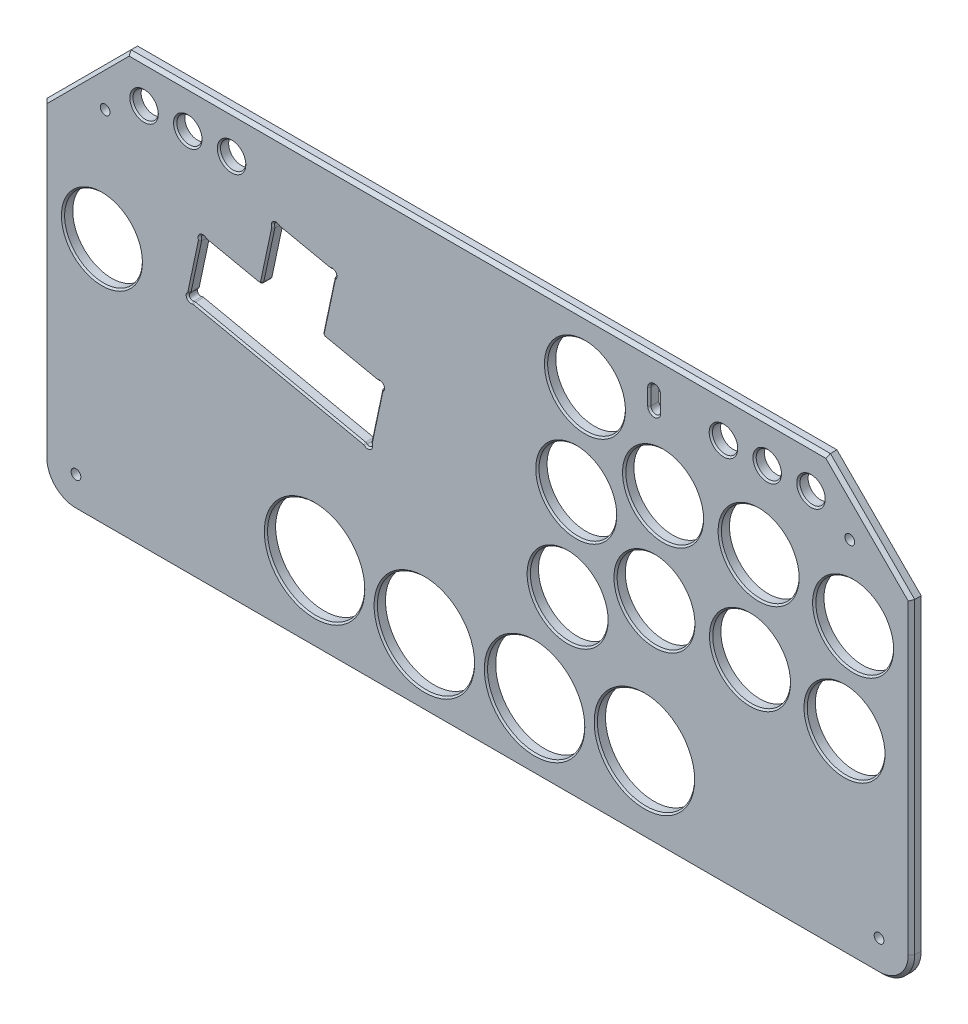
SolidWorks part; units mm, degrees
ref_plane "Front Plane" through (0, 0, 0) normal (0, 0, 1) x (1, 0, 0)
ref_plane "Top Plane" through (0, 0, 0) normal (0, 1, 0) x (1, 0, 0)
ref_plane "Right Plane" through (0, 0, 0) normal (1, 0, 0) x (0, 0, -1)
sketch "Sketch1" plane through (0, 0, 0) normal (0, 0, 1) x (1, 0, 0)
  line L0 (157.8919, 26.2701) -> (191.7747, 29.0915)
  line L1 (157.8919, 26.2701) -> (191.7747, 26.2701)
  line L2 (157.8919, 26.2701) -> (157.8919, 29.0915)
  line L3 (157.8919, 29.0915) -> (191.7747, 29.0915)
  line L4 (191.7747, 26.2701) -> (191.7747, 29.0915)
  line L5 (123.8919, 26.2701) -> (90.0092, 26.2701)
  line L6 (123.8919, 26.2701) -> (123.8919, 29.0915)
  line L7 (123.8919, 29.0915) -> (90.0092, 29.0915)
  line L8 (90.0092, 26.2701) -> (90.0092, 29.0915)
  line L9 (90.0092, 29.0915) -> (123.8919, 26.2701)
  line L10 (168.0919, 58.3601) -> (194.8735, 70.7292)
  line L11 (168.0919, 58.3601) -> (194.8735, 58.3601)
  line L12 (168.0919, 58.3601) -> (168.0919, 70.7292)
  line L13 (168.0919, 70.7292) -> (194.8735, 70.7292)
  line L14 (194.8735, 58.3601) -> (194.8735, 70.7292)
  line L15 (194.8735, 70.7292) -> (224.3587, 70.7292)
  line L16 (194.8735, 70.7292) -> (194.8735, 69.7923)
  line L17 (194.8735, 69.7923) -> (224.3587, 69.7923)
  line L18 (224.3587, 70.7292) -> (224.3587, 69.7923)
  line L19 (224.3587, 69.7923) -> (253.5106, 69.7923)
  line L20 (224.3587, 69.7923) -> (224.3587, 65.2742)
  line L21 (224.3587, 65.2742) -> (253.5106, 65.2742)
  line L22 (253.5106, 69.7923) -> (253.5106, 65.2742)
  line L23 (224.3587, 69.7923) -> (194.8735, 70.7292)
  line L24 (253.5106, 65.2742) -> (224.3587, 69.7923)
  line L25 (170.7502, 87.7401) -> (168.0919, 58.3601)
  line L26 (168.0919, 58.3601) -> (170.7502, 58.3601)
  line L27 (168.0919, 58.3601) -> (168.0919, 87.7401)
  line L28 (168.0919, 87.7401) -> (170.7502, 87.7401)
  line L29 (170.7502, 58.3601) -> (170.7502, 87.7401)
  line L30 (52.9966, 89.4705) -> (24.4119, 82.1791)
  line L31 (24.4119, 82.1791) -> (52.9966, 82.1791)
  line L32 (24.4119, 82.1791) -> (24.4119, 89.4705)
  line L33 (24.4119, 89.4705) -> (52.9966, 89.4705)
  line L34 (52.9966, 82.1791) -> (52.9966, 89.4705)
  line L35 (82.4966, 89.4705) -> (109.0019, 89.4705)
  line L36 (82.4966, 89.4705) -> (82.4966, 76.5201)
  line L37 (82.4966, 76.5201) -> (109.0019, 76.5201)
  line L38 (109.0019, 89.4705) -> (109.0019, 76.5201)
  line L39 (92.4554, 117.2387) -> (82.4966, 117.2387)
  line L40 (92.4554, 117.2387) -> (92.4554, 89.4705)
  line L41 (92.4554, 89.4705) -> (82.4966, 89.4705)
  line L42 (82.4966, 117.2387) -> (82.4966, 89.4705)
  line L43 (92.4554, 117.2387) -> (82.4966, 89.4705)
  line L44 (109.0019, 76.5201) -> (82.4966, 89.4705)
  circle A0 centre (123.8919, 26.2701) radius 14.25
  circle A1 centre (157.8919, 26.2701) radius 14.25
  circle A2 centre (90.0092, 29.0915) radius 14.25
  circle A3 centre (191.7747, 29.0915) radius 14.25
  circle A4 centre (82.4966, 89.4705) radius 11.25
  circle A5 centre (92.4554, 117.2387) radius 11.25
  circle A6 centre (52.9966, 89.4705) radius 11.25
  circle A7 centre (109.0019, 76.5201) radius 11.25
  circle A8 centre (24.4119, 82.1791) radius 11.25
  circle A9 centre (170.7502, 87.7401) radius 11.25
  circle A10 centre (168.0919, 58.3601) radius 11.25
  circle A11 centre (197.5318, 100.1092) radius 11.25
  circle A12 centre (194.8735, 70.7292) radius 11.25
  circle A13 centre (227.0169, 99.1723) radius 11.25
  circle A14 centre (224.3587, 69.7923) radius 11.25
  circle A15 centre (256.1689, 94.6541) radius 11.25
  circle A16 centre (253.5106, 65.2742) radius 11.25
  circle A17 centre (24.4119, 82.1791) radius 12
  circle A18 centre (52.9966, 89.4705) radius 12
  circle A19 centre (92.4554, 117.2387) radius 12
  circle A20 centre (82.4966, 89.4705) radius 12
  circle A21 centre (109.0019, 76.5201) radius 12
  circle A22 centre (168.0919, 58.3601) radius 12
  circle A23 centre (194.8735, 70.7292) radius 12
  circle A24 centre (224.3587, 69.7923) radius 12
  circle A25 centre (253.5106, 65.2742) radius 12
  circle A26 centre (256.1689, 94.6541) radius 12
  circle A27 centre (227.0169, 99.1723) radius 12
  circle A28 centre (197.5318, 100.1092) radius 12
  circle A29 centre (170.7502, 87.7401) radius 12
  circle A30 centre (191.7747, 29.0915) radius 15
  circle A31 centre (157.8919, 26.2701) radius 15
  circle A32 centre (123.8919, 26.2701) radius 15
  circle A33 centre (90.0092, 29.0915) radius 15
  circle A34 centre (173.429, 117.1182) radius 11.25
  circle A35 centre (173.429, 117.1182) radius 12
  dimension "D1" = 28.5
  dimension "D2" = 22.5
  dimension "D3" = 0.75
  dimension "D4" = 0.75
  dimension "D34" = 34
  dimension "D5" = 29.5
  dimension "D6" = 29.5
  dimension "D7" = 29.5
  dimension "D8" = 29.5
  dimension "D9" = 29.5
  dimension "D10" = 29.5
  dimension "D11" = 29.5
  dimension "D12" = 29.5
  dimension "D13" = 29.5
  dimension "D14" = 29.5
  dimension "D15" = 29.5
  dimension "D16" = 29.5
  dimension "D17" = 29.5
  dimension "D18" = 29.5
  dimension "D19" = 34
  dimension "D20" = 34
  dimension "D21" = 32.09
  dimension "D22" = 10.2
  dimension "D23" = 4.76
  dimension "D24" = 4.76
  dimension "D25" = 24.79
  dimension "D26" = 1.82
  dimension "D27" = 8.81
  dimension "D28" = 84.83
  dimension "D29" = 75.69
  dimension "D30" = 70.27
  dimension "D31" = 26.04
  dimension "D32" = 14.89
  dimension "D33" = 50.25
  dimension "D35" = 29.5
  dimension "D36" = 29.5
sketch "Sketch4" plane through (-30.2083, 20.075, 0) normal (0, 0, 1) x (0.9781, -0.2079, 0)
  line L0 (86.1706, 94.1917) -> (105.2206, 75.1417)
  line L1 (67.1206, 94.1917) -> (86.1706, 94.1917)
  line L2 (67.1206, 94.1917) -> (67.1206, 75.1417)
  line L3 (67.1206, 75.1417) -> (86.1706, 75.1417)
  line L4 (86.1706, 94.1917) -> (86.1706, 75.1417)
  line L5 (86.1706, 94.1917) -> (105.2206, 94.1917)
  line L6 (86.1706, 94.1917) -> (86.1706, 75.1417)
  line L7 (86.1706, 75.1417) -> (105.2206, 75.1417)
  line L8 (105.2206, 94.1917) -> (105.2206, 75.1417)
  line L9 (105.2206, 94.1917) -> (124.2706, 94.1917)
  line L10 (105.2206, 94.1917) -> (105.2206, 75.1417)
  line L11 (105.2206, 75.1417) -> (124.2706, 75.1417)
  line L12 (124.2706, 94.1917) -> (124.2706, 75.1417)
  line L13 (86.1706, 94.1917) -> (105.2206, 94.1917)
  line L14 (86.1706, 94.1917) -> (86.1706, 113.2417)
  line L15 (86.1706, 113.2417) -> (105.2206, 113.2417)
  line L16 (105.2206, 94.1917) -> (105.2206, 113.2417)
  line L17 (66.9585, 85.1784) -> (124.4326, 84.1551)
  point P14 (95.6956, 84.6667)
  point P15 (95.6956, 84.6667)
  dimension "D1" = 19.05
sketch "Sketch9" plane through (0, 0, 0) normal (0, 0, 1) x (1, 0, 0)
  line L1 (17.3619, 89.2291) -> (31.4619, 89.2291)
  line L2 (17.3619, 89.2291) -> (17.3619, 75.1291)
  line L3 (17.3619, 75.1291) -> (31.4619, 75.1291)
  line L4 (31.4619, 89.2291) -> (31.4619, 75.1291)
  line L5 (45.9466, 96.5205) -> (60.0466, 96.5205)
  line L6 (45.9466, 96.5205) -> (45.9466, 82.4205)
  line L7 (45.9466, 82.4205) -> (60.0466, 82.4205)
  line L8 (60.0466, 96.5205) -> (60.0466, 82.4205)
  line L9 (75.4466, 96.5205) -> (89.5466, 96.5205)
  line L10 (75.4466, 96.5205) -> (75.4466, 82.4205)
  line L11 (75.4466, 82.4205) -> (89.5466, 82.4205)
  line L12 (89.5466, 96.5205) -> (89.5466, 82.4205)
  line L13 (101.9519, 83.5701) -> (116.0519, 83.5701)
  line L14 (101.9519, 83.5701) -> (101.9519, 69.4701)
  line L15 (101.9519, 69.4701) -> (116.0519, 69.4701)
  line L16 (116.0519, 83.5701) -> (116.0519, 69.4701)
  line L17 (85.4054, 124.2887) -> (99.5054, 124.2887)
  line L18 (85.4054, 124.2887) -> (85.4054, 110.1887)
  line L19 (85.4054, 110.1887) -> (99.5054, 110.1887)
  line L20 (99.5054, 124.2887) -> (99.5054, 110.1887)
  line L21 (82.9592, 36.1415) -> (97.0592, 36.1415)
  line L22 (82.9592, 36.1415) -> (82.9592, 22.0415)
  line L23 (82.9592, 22.0415) -> (97.0592, 22.0415)
  line L24 (97.0592, 36.1415) -> (97.0592, 22.0415)
  line L25 (116.8419, 33.3201) -> (130.9419, 33.3201)
  line L26 (116.8419, 33.3201) -> (116.8419, 19.2201)
  line L27 (116.8419, 19.2201) -> (130.9419, 19.2201)
  line L28 (130.9419, 33.3201) -> (130.9419, 19.2201)
  line L29 (150.8419, 33.3201) -> (164.9419, 33.3201)
  line L30 (150.8419, 33.3201) -> (150.8419, 19.2201)
  line L31 (150.8419, 19.2201) -> (164.9419, 19.2201)
  line L32 (164.9419, 33.3201) -> (164.9419, 19.2201)
  line L33 (184.7247, 36.1415) -> (198.8247, 36.1415)
  line L34 (184.7247, 36.1415) -> (184.7247, 22.0415)
  line L35 (184.7247, 22.0415) -> (198.8247, 22.0415)
  line L36 (198.8247, 36.1415) -> (198.8247, 22.0415)
  line L37 (260.5606, 58.2242) -> (246.4606, 58.2242)
  line L38 (260.5606, 58.2242) -> (260.5606, 72.3242)
  line L39 (260.5606, 72.3242) -> (246.4606, 72.3242)
  line L40 (246.4606, 58.2242) -> (246.4606, 72.3242)
  line L41 (217.3087, 76.8423) -> (231.4087, 76.8423)
  line L42 (217.3087, 76.8423) -> (217.3087, 62.7423)
  line L43 (217.3087, 62.7423) -> (231.4087, 62.7423)
  line L44 (231.4087, 76.8423) -> (231.4087, 62.7423)
  line L45 (187.8235, 77.7792) -> (201.9235, 77.7792)
  line L46 (187.8235, 77.7792) -> (187.8235, 63.6792)
  line L47 (187.8235, 63.6792) -> (201.9235, 63.6792)
  line L48 (201.9235, 77.7792) -> (201.9235, 63.6792)
  line L49 (161.0419, 65.4101) -> (175.1419, 65.4101)
  line L50 (161.0419, 65.4101) -> (161.0419, 51.3101)
  line L51 (161.0419, 51.3101) -> (175.1419, 51.3101)
  line L52 (175.1419, 65.4101) -> (175.1419, 51.3101)
  line L53 (163.7002, 94.7901) -> (177.8002, 94.7901)
  line L54 (163.7002, 94.7901) -> (163.7002, 80.6901)
  line L55 (163.7002, 80.6901) -> (177.8002, 80.6901)
  line L56 (177.8002, 94.7901) -> (177.8002, 80.6901)
  line L57 (190.4818, 107.1592) -> (204.5818, 107.1592)
  line L58 (190.4818, 107.1592) -> (190.4818, 93.0592)
  line L59 (190.4818, 93.0592) -> (204.5818, 93.0592)
  line L60 (204.5818, 107.1592) -> (204.5818, 93.0592)
  line L61 (219.9669, 106.2223) -> (234.0669, 106.2223)
  line L62 (219.9669, 106.2223) -> (219.9669, 92.1223)
  line L63 (219.9669, 92.1223) -> (234.0669, 92.1223)
  line L64 (234.0669, 106.2223) -> (234.0669, 92.1223)
  line L65 (249.1189, 101.7041) -> (263.2189, 101.7041)
  line L66 (249.1189, 101.7041) -> (249.1189, 87.6041)
  line L67 (249.1189, 87.6041) -> (263.2189, 87.6041)
  line L68 (263.2189, 101.7041) -> (263.2189, 87.6041)
  line L69 (166.379, 124.1682) -> (180.479, 124.1682)
  line L70 (166.379, 124.1682) -> (166.379, 110.0682)
  line L71 (166.379, 110.0682) -> (180.479, 110.0682)
  line L72 (180.479, 124.1682) -> (180.479, 110.0682)
  point P72 (24.4119, 89.2291)
  point P74 (52.9966, 96.5205)
  point P76 (82.4966, 96.5205)
  point P78 (92.4554, 124.2887)
  point P80 (109.0019, 83.5701)
  point P82 (90.0092, 36.1415)
  point P84 (123.8919, 33.3201)
  point P86 (157.8919, 33.3201)
  point P88 (191.7747, 36.1415)
  point P90 (168.0919, 65.4101)
  point P92 (170.7502, 94.7901)
  point P94 (173.429, 124.1682)
  point P96 (197.5318, 107.1592)
  point P98 (227.0169, 106.2223)
  point P100 (256.1689, 101.7041)
  point P102 (194.8735, 77.7792)
  point P104 (224.3587, 76.8423)
  point P106 (253.5106, 72.3242)
  point P108 (17.3619, 82.1791)
  point P109 (45.9466, 89.4705)
  point P110 (75.4466, 89.4705)
  point P111 (101.9519, 76.5201)
  point P112 (85.4054, 117.2387)
  point P113 (82.9592, 29.0915)
  point P114 (116.8419, 26.2701)
  point P115 (150.8419, 26.2701)
  point P116 (184.7247, 29.0915)
  point P118 (161.0419, 58.3601)
  point P119 (187.8235, 70.7292)
  point P120 (217.3087, 69.7923)
  point P121 (246.4606, 65.2742)
  point P122 (163.7002, 87.7401)
  point P123 (190.4818, 100.1092)
  point P124 (219.9669, 99.1723)
  point P125 (249.1189, 94.6541)
  point P126 (166.379, 117.1182)
  dimension "D1" = 14.1
sketch "Sketch10" plane through (-22.0981, 19.3454, 0) normal (0, 0, 1) x (0.9781, -0.2079, 0)
  line L1 (61.5108, 90.7441) -> (75.6108, 90.7441)
  line L2 (61.5108, 90.7441) -> (61.5108, 76.6441)
  line L3 (61.5108, 76.6441) -> (75.6108, 76.6441)
  line L4 (75.6108, 90.7441) -> (75.6108, 76.6441)
  line L5 (80.5608, 90.7441) -> (94.6608, 90.7441)
  line L6 (80.5608, 90.7441) -> (80.5608, 76.6441)
  line L7 (80.5608, 76.6441) -> (94.6608, 76.6441)
  line L8 (94.6608, 90.7441) -> (94.6608, 76.6441)
  line L9 (99.6108, 90.7441) -> (113.7108, 90.7441)
  line L10 (99.6108, 90.7441) -> (99.6108, 76.6441)
  line L11 (99.6108, 76.6441) -> (113.7108, 76.6441)
  line L12 (113.7108, 90.7441) -> (113.7108, 76.6441)
  line L13 (80.5608, 109.7941) -> (94.6608, 109.7941)
  line L14 (80.5608, 109.7941) -> (80.5608, 95.6941)
  line L15 (80.5608, 95.6941) -> (94.6608, 95.6941)
  line L16 (94.6608, 109.7941) -> (94.6608, 95.6941)
  line L17 (50.5121, 89.6359) -> (53.4436, 75.8441) construction
  line L18 (59.0358, 93.2191) -> (78.0858, 93.2191) construction
  line L19 (78.0858, 112.2691) -> (97.1358, 112.2691) construction
  line L20 (97.1358, 93.2191) -> (116.1858, 93.2191) construction
  line L21 (78.0858, 93.2191) -> (78.0858, 112.2691) construction
  line L23 (59.0358, 93.2191) -> (59.0358, 74.1691) construction
  point P16 (75.6108, 83.6941)
  point P17 (94.6608, 83.6941)
  point P18 (113.7108, 83.6941)
  point P19 (87.6108, 90.7441)
  point P20 (87.6108, 109.7941)
  point P23 (68.5608, 90.7441)
  point P26 (68.5608, 93.2191)
  point P29 (87.6108, 112.2691)
  point P30 (106.6608, 90.7441)
  point P33 (106.6608, 93.2191)
  point P34 (80.5608, 102.7441)
  point P37 (78.0858, 102.7441)
  point P42 (59.0358, 83.6941)
  point P43 (61.5108, 83.6941)
sketch "Sketch14" plane through (0, 0, 0) normal (0, 0, 1) x (1, 0, 0)
  line L0 (165.1144, 80.6901) -> (163.7002, 82.1043)
  line L1 (163.7002, 93.3758) -> (165.1144, 94.7901)
  line L2 (177.8002, 93.3758) -> (176.386, 94.7901)
  line L3 (179.0648, 110.0682) -> (180.479, 111.4824)
  line L4 (166.379, 111.4824) -> (167.7932, 110.0682)
  line L5 (166.379, 122.754) -> (167.7932, 124.1682)
  line L6 (179.0648, 124.1682) -> (180.479, 122.754)
  line L7 (203.1676, 93.0592) -> (204.5818, 94.4734)
  line L8 (17.3619, 89.2291) -> (17.3619, 75.1291) construction
  line L9 (17.3619, 89.2291) -> (31.4619, 89.2291) construction
  line L10 (17.3619, 87.8149) -> (18.7761, 89.2291)
  line L11 (17.3619, 75.1291) -> (31.4619, 75.1291) construction
  line L12 (31.4619, 89.2291) -> (31.4619, 75.1291) construction
  line L13 (45.9466, 96.5205) -> (60.0466, 96.5205) construction
  line L14 (60.0466, 96.5205) -> (60.0466, 82.4205) construction
  line L15 (45.9466, 96.5205) -> (45.9466, 82.4205) construction
  line L16 (45.9466, 82.4205) -> (60.0466, 82.4205) construction
  line L17 (85.4054, 124.2887) -> (85.4054, 110.1887) construction
  line L18 (85.4054, 124.2887) -> (99.5054, 124.2887) construction
  line L19 (99.5054, 124.2887) -> (99.5054, 110.1887) construction
  line L20 (85.4054, 110.1887) -> (99.5054, 110.1887) construction
  line L21 (101.9519, 83.5701) -> (101.9519, 69.4701) construction
  line L22 (101.9519, 83.5701) -> (116.0519, 83.5701) construction
  line L23 (116.0519, 83.5701) -> (116.0519, 69.4701) construction
  line L24 (101.9519, 69.4701) -> (116.0519, 69.4701) construction
  line L25 (91.2712, 73.6044) -> (105.0631, 70.6729) construction
  line L26 (107.9947, 84.4647) -> (105.0631, 70.6729) construction
  line L27 (94.2028, 87.3963) -> (107.9947, 84.4647) construction
  line L28 (94.2028, 87.3963) -> (91.2712, 73.6044) construction
  line L29 (72.6375, 77.5651) -> (86.4294, 74.6336) construction
  line L30 (89.361, 88.4255) -> (86.4294, 74.6336) construction
  line L31 (75.5691, 91.357) -> (89.361, 88.4255) construction
  line L32 (75.5691, 91.357) -> (72.6375, 77.5651) construction
  line L33 (56.9354, 95.3177) -> (54.0038, 81.5259) construction
  line L34 (56.9354, 95.3177) -> (70.7273, 92.3862) construction
  line L35 (70.7273, 92.3862) -> (67.7957, 78.5943) construction
  line L36 (54.0038, 81.5259) -> (67.7957, 78.5943) construction
  line L37 (76.5983, 96.1988) -> (90.3901, 93.2673) construction
  line L38 (93.3217, 107.0592) -> (90.3901, 93.2673) construction
  line L39 (79.5298, 109.9907) -> (76.5983, 96.1988) construction
  line L40 (79.5298, 109.9907) -> (93.3217, 107.0592) construction
  line L41 (82.9592, 36.1415) -> (82.9592, 22.0415) construction
  line L42 (82.9592, 36.1415) -> (97.0592, 36.1415) construction
  line L43 (82.9592, 22.0415) -> (97.0592, 22.0415) construction
  line L44 (97.0592, 36.1415) -> (97.0592, 22.0415) construction
  line L45 (116.8419, 33.3201) -> (116.8419, 19.2201) construction
  line L46 (116.8419, 33.3201) -> (130.9419, 33.3201) construction
  line L47 (116.8419, 19.2201) -> (130.9419, 19.2201) construction
  line L48 (130.9419, 33.3201) -> (130.9419, 19.2201) construction
  line L49 (150.8419, 33.3201) -> (150.8419, 19.2201) construction
  line L50 (150.8419, 33.3201) -> (164.9419, 33.3201) construction
  line L51 (164.9419, 33.3201) -> (164.9419, 19.2201) construction
  line L52 (150.8419, 19.2201) -> (164.9419, 19.2201) construction
  line L53 (184.7247, 36.1415) -> (184.7247, 22.0415) construction
  line L54 (184.7247, 22.0415) -> (198.8247, 22.0415) construction
  line L55 (198.8247, 36.1415) -> (198.8247, 22.0415) construction
  line L56 (184.7247, 36.1415) -> (198.8247, 36.1415) construction
  line L57 (161.0419, 65.4101) -> (175.1419, 65.4101) construction
  line L58 (175.1419, 65.4101) -> (175.1419, 51.3101) construction
  line L59 (161.0419, 51.3101) -> (175.1419, 51.3101) construction
  line L60 (161.0419, 65.4101) -> (161.0419, 51.3101) construction
  line L61 (187.8235, 77.7792) -> (187.8235, 63.6792) construction
  line L62 (187.8235, 77.7792) -> (201.9235, 77.7792) construction
  line L63 (187.8235, 63.6792) -> (201.9235, 63.6792) construction
  line L64 (201.9235, 77.7792) -> (201.9235, 63.6792) construction
  line L65 (217.3087, 76.8423) -> (217.3087, 62.7423) construction
  line L66 (217.3087, 76.8423) -> (231.4087, 76.8423) construction
  line L67 (231.4087, 76.8423) -> (231.4087, 62.7423) construction
  line L68 (217.3087, 62.7423) -> (231.4087, 62.7423) construction
  line L69 (260.5606, 58.2242) -> (246.4606, 58.2242) construction
  line L70 (260.5606, 58.2242) -> (260.5606, 72.3242) construction
  line L71 (246.4606, 58.2242) -> (246.4606, 72.3242) construction
  line L72 (260.5606, 72.3242) -> (246.4606, 72.3242) construction
  line L73 (249.1189, 101.7041) -> (263.2189, 101.7041) construction
  line L74 (263.2189, 101.7041) -> (263.2189, 87.6041) construction
  line L75 (249.1189, 87.6041) -> (263.2189, 87.6041) construction
  line L76 (249.1189, 101.7041) -> (249.1189, 87.6041) construction
  line L77 (219.9669, 106.2223) -> (219.9669, 92.1223) construction
  line L78 (219.9669, 106.2223) -> (234.0669, 106.2223) construction
  line L79 (234.0669, 106.2223) -> (234.0669, 92.1223) construction
  line L80 (219.9669, 92.1223) -> (234.0669, 92.1223) construction
  line L81 (190.4818, 107.1592) -> (204.5818, 107.1592) construction
  line L82 (204.5818, 107.1592) -> (204.5818, 93.0592) construction
  line L83 (190.4818, 93.0592) -> (204.5818, 93.0592) construction
  line L84 (190.4818, 107.1592) -> (190.4818, 93.0592) construction
  line L85 (163.7002, 94.7901) -> (177.8002, 94.7901) construction
  line L86 (177.8002, 94.7901) -> (177.8002, 80.6901) construction
  line L87 (163.7002, 80.6901) -> (177.8002, 80.6901) construction
  line L88 (163.7002, 94.7901) -> (163.7002, 80.6901) construction
  line L89 (180.479, 124.1682) -> (180.479, 110.0682) construction
  line L90 (166.379, 110.0682) -> (180.479, 110.0682) construction
  line L91 (166.379, 124.1682) -> (166.379, 110.0682) construction
  line L92 (166.379, 124.1682) -> (180.479, 124.1682) construction
  line L93 (17.3619, 76.5433) -> (18.7761, 75.1291)
  line L94 (30.0477, 75.1291) -> (31.4619, 76.5433)
  line L95 (31.4619, 87.8149) -> (30.0477, 89.2291)
  line L96 (45.9466, 95.1063) -> (47.3608, 96.5205)
  line L97 (45.9466, 83.8347) -> (47.3608, 82.4205)
  line L98 (54.2979, 82.9092) -> (55.3871, 81.2318)
  line L99 (58.6323, 82.4205) -> (60.0466, 83.8347)
  line L100 (56.6413, 93.9344) -> (58.3187, 95.0237)
  line L101 (58.6323, 96.5205) -> (60.0466, 95.1063)
  line L102 (69.3439, 92.6802) -> (70.4332, 91.0029)
  line L103 (68.0897, 79.9776) -> (66.4124, 78.8883)
  line L104 (75.2751, 89.9737) -> (76.9524, 91.063)
  line L105 (72.9316, 78.9484) -> (74.0208, 77.2711)
  line L106 (85.0461, 74.9276) -> (86.7234, 76.0169)
  line L107 (89.0669, 87.0421) -> (87.9777, 88.7195)
  line L108 (89.0068, 93.5613) -> (90.6842, 94.6506)
  line L109 (76.8923, 97.5822) -> (77.9816, 95.9048)
  line L110 (91.9384, 107.3532) -> (93.0277, 105.6759)
  line L111 (79.2358, 108.6074) -> (80.9131, 109.6967)
  line L112 (85.4054, 111.6029) -> (86.8196, 110.1887)
  line L113 (98.0912, 110.1887) -> (99.5054, 111.6029)
  line L114 (98.0912, 124.2887) -> (99.5054, 122.8745)
  line L115 (85.4054, 122.8745) -> (86.8196, 124.2887)
  line L116 (93.9088, 86.013) -> (95.5861, 87.1023)
  line L117 (91.5653, 74.9877) -> (92.6546, 73.3104)
  line L118 (103.6798, 70.9669) -> (105.3572, 72.0562)
  line L119 (106.6114, 84.7588) -> (107.7006, 83.0814)
  line L120 (101.9519, 82.1559) -> (103.3662, 83.5701)
  line L121 (101.9519, 70.8843) -> (103.3662, 69.4701)
  line L122 (114.6377, 69.4701) -> (116.0519, 70.8843)
  line L123 (116.0519, 82.1559) -> (114.6377, 83.5701)
  line L124 (82.9592, 34.7272) -> (84.3734, 36.1415)
  line L125 (82.9592, 23.4557) -> (84.3734, 22.0415)
  line L126 (95.645, 22.0415) -> (97.0592, 23.4557)
  line L127 (97.0592, 34.7272) -> (95.645, 36.1415)
  line L128 (116.8419, 31.9059) -> (118.2562, 33.3201)
  line L129 (116.8419, 20.6343) -> (118.2562, 19.2201)
  line L130 (129.5277, 19.2201) -> (130.9419, 20.6343)
  line L131 (130.9419, 31.9059) -> (129.5277, 33.3201)
  line L132 (150.8419, 31.9059) -> (152.2562, 33.3201)
  line L133 (150.8419, 20.6343) -> (152.2562, 19.2201)
  line L134 (163.5277, 19.2201) -> (164.9419, 20.6343)
  line L135 (164.9419, 31.9059) -> (163.5277, 33.3201)
  line L136 (184.7247, 34.7272) -> (186.1389, 36.1415)
  line L137 (184.7247, 23.4557) -> (186.1389, 22.0415)
  line L138 (197.4105, 22.0415) -> (198.8247, 23.4557)
  line L139 (198.8247, 34.7272) -> (197.4105, 36.1415)
  line L140 (173.7277, 51.3101) -> (175.1419, 52.7243)
  line L141 (161.0419, 52.7243) -> (162.4562, 51.3101)
  line L142 (161.0419, 63.9959) -> (162.4562, 65.4101)
  line L143 (173.7277, 65.4101) -> (175.1419, 63.9959)
  line L144 (187.8235, 65.0934) -> (189.2378, 63.6792)
  line L145 (200.5093, 63.6792) -> (201.9235, 65.0934)
  line L146 (200.5093, 77.7792) -> (201.9235, 76.365)
  line L147 (187.8235, 76.365) -> (189.2378, 77.7792)
  line L148 (176.386, 80.6901) -> (177.8002, 82.1043)
  line L149 (204.5818, 105.745) -> (203.1676, 107.1592)
  line L150 (191.896, 107.1592) -> (190.4818, 105.745)
  line L151 (190.4818, 94.4734) -> (191.896, 93.0592)
  line L152 (219.9669, 104.8081) -> (221.3812, 106.2223)
  line L153 (232.6527, 106.2223) -> (234.0669, 104.8081)
  line L154 (234.0669, 93.5365) -> (232.6527, 92.1223)
  line L155 (219.9669, 93.5365) -> (221.3812, 92.1223)
  line L156 (229.9944, 76.8423) -> (231.4087, 75.4281)
  line L157 (217.3087, 75.4281) -> (218.7229, 76.8423)
  line L158 (217.3087, 64.1565) -> (218.7229, 62.7423)
  line L159 (229.9944, 62.7423) -> (231.4087, 64.1565)
  line L160 (259.1464, 72.3242) -> (260.5606, 70.9099)
  line L161 (246.4606, 70.9099) -> (247.8748, 72.3242)
  line L162 (259.1464, 58.2242) -> (260.5606, 59.6384)
  line L163 (247.8748, 58.2242) -> (246.4606, 59.6384)
  line L164 (261.8047, 87.6041) -> (263.2189, 89.0183)
  line L165 (249.1189, 89.0183) -> (250.5331, 87.6041)
  line L166 (249.1189, 100.2899) -> (250.5331, 101.7041)
  line L167 (261.8047, 101.7041) -> (263.2189, 100.2899)
  line L168 (75.4466, 96.5205) -> (75.4466, 82.4205) construction
  line L169 (75.4466, 96.5205) -> (89.5466, 96.5205) construction
  line L170 (89.5466, 96.5205) -> (89.5466, 82.4205) construction
  line L171 (75.4466, 82.4205) -> (89.5466, 82.4205) construction
  line L172 (76.8608, 96.5205) -> (75.4466, 95.1063)
  line L173 (88.1323, 96.5205) -> (89.5466, 95.1063)
  line L174 (89.5466, 83.8347) -> (88.1323, 82.4205)
  line L175 (75.4466, 83.8347) -> (76.8608, 82.4205)
  arc A0 (17.3619, 87.8149) -> (18.7761, 89.2291) centre (18.069, 88.522) cw
  arc A1 (18.7761, 75.1291) -> (17.3619, 76.5433) centre (18.069, 75.8362) cw
  arc A2 (31.4619, 76.5433) -> (30.0477, 75.1291) centre (30.7548, 75.8362) cw
  arc A3 (30.0477, 89.2291) -> (31.4619, 87.8149) centre (30.7548, 88.522) cw
  arc A4 (58.6323, 96.5205) -> (60.0466, 95.1063) centre (59.3394, 95.8134) cw
  arc A5 (45.9466, 95.1063) -> (47.3608, 96.5205) centre (46.6537, 95.8134) cw
  arc A6 (47.3608, 82.4205) -> (45.9466, 83.8347) centre (46.6537, 83.1276) cw
  arc A7 (60.0466, 83.8347) -> (58.6323, 82.4205) centre (59.3394, 83.1276) cw
  arc A8 (85.4054, 122.8745) -> (86.8196, 124.2887) centre (86.1125, 123.5816) cw
  arc A9 (98.0912, 124.2887) -> (99.5054, 122.8745) centre (98.7983, 123.5816) cw
  arc A10 (99.5054, 111.6029) -> (98.0912, 110.1887) centre (98.7983, 110.8958) cw
  arc A11 (85.4054, 111.6029) -> (86.8196, 110.1887) centre (86.1125, 110.8958) ccw
  arc A12 (101.9519, 82.1559) -> (103.3662, 83.5701) centre (102.6591, 82.863) cw
  arc A13 (114.6377, 83.5701) -> (116.0519, 82.1559) centre (115.3448, 82.863) cw
  arc A14 (116.0519, 70.8843) -> (114.6377, 69.4701) centre (115.3448, 70.1772) cw
  arc A15 (101.9519, 70.8843) -> (103.3662, 69.4701) centre (102.6591, 70.1772) ccw
  arc A16 (103.6798, 70.9669) -> (105.3572, 72.0562) centre (104.5185, 71.5115) ccw
  arc A17 (106.6114, 84.7588) -> (107.7006, 83.0814) centre (107.156, 83.9201) cw
  arc A18 (93.9088, 86.013) -> (95.5861, 87.1023) centre (94.7474, 86.5576) cw
  arc A19 (91.5653, 74.9877) -> (92.6546, 73.3104) centre (92.1099, 74.1491) ccw
  arc A20 (85.0461, 74.9276) -> (86.7234, 76.0169) centre (85.8848, 75.4722) ccw
  arc A21 (87.9777, 88.7195) -> (89.0669, 87.0421) centre (88.5223, 87.8808) cw
  arc A22 (75.2751, 89.9737) -> (76.9524, 91.063) centre (76.1137, 90.5183) cw
  arc A23 (72.9316, 78.9484) -> (74.0208, 77.2711) centre (73.4762, 78.1098) ccw
  arc A24 (56.6413, 93.9344) -> (58.3187, 95.0237) centre (57.48, 94.4791) cw
  arc A25 (69.3439, 92.6802) -> (70.4332, 91.0029) centre (69.8886, 91.8415) cw
  arc A26 (68.0897, 79.9776) -> (66.4124, 78.8883) centre (67.2511, 79.433) cw
  arc A27 (54.2979, 82.9092) -> (55.3871, 81.2318) centre (54.8425, 82.0705) ccw
  arc A28 (89.0068, 93.5613) -> (90.6842, 94.6506) centre (89.8455, 94.106) ccw
  arc A29 (76.8923, 97.5822) -> (77.9816, 95.9048) centre (77.4369, 96.7435) ccw
  arc A30 (79.2358, 108.6074) -> (80.9131, 109.6967) centre (80.0744, 109.1521) cw
  arc A31 (91.9384, 107.3532) -> (93.0277, 105.6759) centre (92.483, 106.5145) cw
  arc A32 (82.9592, 34.7272) -> (84.3734, 36.1415) centre (83.6663, 35.4344) cw
  arc A33 (82.9592, 23.4557) -> (84.3734, 22.0415) centre (83.6663, 22.7486) ccw
  arc A34 (95.645, 22.0415) -> (97.0592, 23.4557) centre (96.3521, 22.7486) ccw
  arc A35 (95.645, 36.1415) -> (97.0592, 34.7272) centre (96.3521, 35.4344) cw
  arc A36 (116.8419, 31.9059) -> (118.2562, 33.3201) centre (117.5491, 32.613) cw
  arc A37 (116.8419, 20.6343) -> (118.2562, 19.2201) centre (117.5491, 19.9272) ccw
  arc A38 (129.5277, 19.2201) -> (130.9419, 20.6343) centre (130.2348, 19.9272) ccw
  arc A39 (129.5277, 33.3201) -> (130.9419, 31.9059) centre (130.2348, 32.613) cw
  arc A40 (150.8419, 31.9059) -> (152.2562, 33.3201) centre (151.5491, 32.613) cw
  arc A41 (163.5277, 33.3201) -> (164.9419, 31.9059) centre (164.2348, 32.613) cw
  arc A42 (164.9419, 20.6343) -> (163.5277, 19.2201) centre (164.2348, 19.9272) cw
  arc A43 (150.8419, 20.6343) -> (152.2562, 19.2201) centre (151.5491, 19.9272) ccw
  arc A44 (184.7247, 23.4557) -> (186.1389, 22.0415) centre (185.4318, 22.7486) ccw
  arc A45 (197.4105, 22.0415) -> (198.8247, 23.4557) centre (198.1176, 22.7486) ccw
  arc A46 (197.4105, 36.1415) -> (198.8247, 34.7272) centre (198.1176, 35.4344) cw
  arc A47 (184.7247, 34.7272) -> (186.1389, 36.1415) centre (185.4318, 35.4344) cw
  arc A48 (173.7277, 65.4101) -> (175.1419, 63.9959) centre (174.4348, 64.703) cw
  arc A49 (175.1419, 52.7243) -> (173.7277, 51.3101) centre (174.4348, 52.0172) cw
  arc A50 (161.0419, 52.7243) -> (162.4562, 51.3101) centre (161.7491, 52.0172) ccw
  arc A51 (161.0419, 63.9959) -> (162.4562, 65.4101) centre (161.7491, 64.703) cw
  arc A52 (187.8235, 76.365) -> (189.2378, 77.7792) centre (188.5306, 77.0721) cw
  arc A53 (187.8235, 65.0934) -> (189.2378, 63.6792) centre (188.5306, 64.3863) ccw
  arc A54 (200.5093, 63.6792) -> (201.9235, 65.0934) centre (201.2164, 64.3863) ccw
  arc A55 (200.5093, 77.7792) -> (201.9235, 76.365) centre (201.2164, 77.0721) cw
  arc A56 (217.3087, 75.4281) -> (218.7229, 76.8423) centre (218.0158, 76.1352) cw
  arc A57 (229.9944, 76.8423) -> (231.4087, 75.4281) centre (230.7016, 76.1352) cw
  arc A58 (231.4087, 64.1565) -> (229.9944, 62.7423) centre (230.7016, 63.4494) cw
  arc A59 (217.3087, 64.1565) -> (218.7229, 62.7423) centre (218.0158, 63.4494) ccw
  arc A60 (259.1464, 58.2242) -> (260.5606, 59.6384) centre (259.8535, 58.9313) ccw
  arc A61 (246.4606, 59.6384) -> (247.8748, 58.2242) centre (247.1677, 58.9313) ccw
  arc A62 (246.4606, 70.9099) -> (247.8748, 72.3242) centre (247.1677, 71.617) cw
  arc A63 (259.1464, 72.3242) -> (260.5606, 70.9099) centre (259.8535, 71.617) cw
  arc A64 (261.8047, 101.7041) -> (263.2189, 100.2899) centre (262.5118, 100.997) cw
  arc A65 (263.2189, 89.0183) -> (261.8047, 87.6041) centre (262.5118, 88.3112) cw
  arc A66 (250.5331, 87.6041) -> (249.1189, 89.0183) centre (249.826, 88.3112) cw
  arc A67 (249.1189, 100.2899) -> (250.5331, 101.7041) centre (249.826, 100.997) cw
  arc A68 (219.9669, 104.8081) -> (221.3812, 106.2223) centre (220.674, 105.5152) cw
  arc A69 (232.6527, 106.2223) -> (234.0669, 104.8081) centre (233.3598, 105.5152) cw
  arc A70 (234.0669, 93.5365) -> (232.6527, 92.1223) centre (233.3598, 92.8294) cw
  arc A71 (221.3812, 92.1223) -> (219.9669, 93.5365) centre (220.674, 92.8294) cw
  arc A72 (203.1676, 107.1592) -> (204.5818, 105.745) centre (203.8747, 106.4521) cw
  arc A73 (204.5818, 94.4734) -> (203.1676, 93.0592) centre (203.8747, 93.7663) cw
  arc A74 (191.896, 93.0592) -> (190.4818, 94.4734) centre (191.1889, 93.7663) cw
  arc A75 (190.4818, 105.745) -> (191.896, 107.1592) centre (191.1889, 106.4521) cw
  arc A76 (176.386, 94.7901) -> (177.8002, 93.3758) centre (177.0931, 94.0829) cw
  arc A77 (177.8002, 82.1043) -> (176.386, 80.6901) centre (177.0931, 81.3972) cw
  arc A78 (165.1144, 80.6901) -> (163.7002, 82.1043) centre (164.4073, 81.3972) cw
  arc A79 (163.7002, 93.3758) -> (165.1144, 94.7901) centre (164.4073, 94.0829) cw
  arc A80 (180.479, 111.4824) -> (179.0648, 110.0682) centre (179.7719, 110.7753) cw
  arc A81 (167.7932, 110.0682) -> (166.379, 111.4824) centre (167.0861, 110.7753) cw
  arc A82 (179.0648, 124.1682) -> (180.479, 122.754) centre (179.7719, 123.4611) cw
  arc A83 (166.379, 122.754) -> (167.7932, 124.1682) centre (167.0861, 123.4611) cw
  arc A84 (75.4466, 95.1063) -> (76.8608, 96.5205) centre (76.1537, 95.8134) cw
  arc A85 (88.1323, 96.5205) -> (89.5466, 95.1063) centre (88.8394, 95.8134) cw
  arc A86 (89.5466, 83.8347) -> (88.1323, 82.4205) centre (88.8394, 83.1276) cw
  arc A87 (76.8608, 82.4205) -> (75.4466, 83.8347) centre (76.1537, 83.1276) cw
  dimension "D1" = 45
  dimension "D2" = 1
  dimension "D71" = 45
  dimension "D3" = 45
  dimension "D4" = 45
  dimension "D5" = 45
  dimension "D6" = 45
  dimension "D7" = 45
  dimension "D8" = 45
  dimension "D9" = 45
  dimension "D10" = 45
  dimension "D11" = 45
  dimension "D12" = 45
  dimension "D13" = 45
  dimension "D14" = 45
  dimension "D15" = 45
  dimension "D16" = 45
  dimension "D17" = 45
  dimension "D18" = 45
  dimension "D19" = 45
  dimension "D20" = 45
  dimension "D21" = 45
  dimension "D22" = 45
  dimension "D23" = 45
  dimension "D24" = 45
  dimension "D25" = 45
  dimension "D26" = 45
  dimension "D27" = 45
  dimension "D28" = 45
  dimension "D29" = 45
  dimension "D30" = 45
  dimension "D31" = 45
  dimension "D32" = 45
  dimension "D33" = 45
  dimension "D34" = 45
  dimension "D35" = 45
  dimension "D36" = 45
  dimension "D37" = 45
  dimension "D38" = 45
  dimension "D39" = 45
  dimension "D40" = 45
  dimension "D41" = 45
  dimension "D42" = 45
  dimension "D43" = 45
  dimension "D44" = 45
  dimension "D45" = 45
  dimension "D46" = 45
  dimension "D47" = 45
  dimension "D48" = 45
  dimension "D49" = 45
  dimension "D50" = 45
  dimension "D51" = 45
  dimension "D52" = 45
  dimension "D53" = 45
  dimension "D54" = 45
  dimension "D55" = 45
  dimension "D56" = 45
  dimension "D57" = 45
  dimension "D58" = 45
  dimension "D59" = 45
  dimension "D60" = 45
  dimension "D61" = 45
  dimension "D62" = 45
  dimension "D63" = 45
  dimension "D64" = 45
  dimension "D65" = 45
  dimension "D66" = 45
  dimension "D67" = 45
  dimension "D68" = 45
  dimension "D69" = 45
  dimension "D70" = 45
  dimension "D72" = 45
  dimension "D73" = 45
  dimension "D74" = 45
  dimension "D75" = 45
  dimension "D76" = 45
  dimension "D77" = 45
  dimension "D78" = 45
  dimension "D79" = 45
  dimension "D80" = 45
  dimension "D81" = 45
  dimension "D82" = 45
  dimension "D83" = 45
  dimension "D84" = 45
  dimension "D85" = 45
  dimension "D86" = 45
  dimension "D87" = 45
  dimension "D88" = 45
  dimension "D89" = 45
sketch "Sketch16" plane through (0, 0, 0) normal (0, 0, 1) x (1, 0, 0)
  line L0 (81.0092, 30.6915) -> (99.0092, 30.6915)
  line L5 (17.3619, 89.2291) -> (17.3619, 75.1291) construction
  line L6 (81.0092, 30.6915) -> (81.0092, 27.4915)
  line L7 (17.3619, 75.1291) -> (31.4619, 75.1291) construction
  line L8 (15.4119, 83.7791) -> (33.4119, 83.7791)
  line L9 (15.4119, 83.7791) -> (15.4119, 80.5791)
  line L10 (15.4119, 80.5791) -> (33.4119, 80.5791)
  line L11 (33.4119, 83.7791) -> (33.4119, 80.5791)
  line L12 (81.0092, 27.4915) -> (99.0092, 27.4915)
  line L13 (99.0092, 30.6915) -> (99.0092, 27.4915)
  line L14 (114.8919, 27.8701) -> (132.8919, 27.8701)
  line L15 (114.8919, 27.8701) -> (114.8919, 24.6701)
  line L16 (114.8919, 24.6701) -> (132.8919, 24.6701)
  line L17 (132.8919, 27.8701) -> (132.8919, 24.6701)
  line L18 (148.8919, 27.8701) -> (166.8919, 27.8701)
  line L19 (148.8919, 27.8701) -> (148.8919, 24.6701)
  line L20 (148.8919, 24.6701) -> (166.8919, 24.6701)
  line L21 (166.8919, 27.8701) -> (166.8919, 24.6701)
  line L22 (182.7747, 30.6915) -> (200.7747, 30.6915)
  line L23 (182.7747, 30.6915) -> (182.7747, 27.4915)
  line L24 (182.7747, 27.4915) -> (200.7747, 27.4915)
  line L25 (200.7747, 30.6915) -> (200.7747, 27.4915)
  line L26 (43.9966, 91.0705) -> (61.9966, 91.0705)
  line L27 (43.9966, 91.0705) -> (43.9966, 87.8705)
  line L28 (43.9966, 87.8705) -> (61.9966, 87.8705)
  line L29 (61.9966, 91.0705) -> (61.9966, 87.8705)
  line L30 (73.4966, 91.0705) -> (91.4966, 91.0705)
  line L31 (73.4966, 91.0705) -> (73.4966, 87.8705)
  line L32 (73.4966, 87.8705) -> (91.4966, 87.8705)
  line L33 (91.4966, 91.0705) -> (91.4966, 87.8705)
  line L34 (100.0019, 78.1201) -> (118.0019, 78.1201)
  line L35 (100.0019, 78.1201) -> (100.0019, 74.9201)
  line L36 (100.0019, 74.9201) -> (118.0019, 74.9201)
  line L37 (118.0019, 78.1201) -> (118.0019, 74.9201)
  line L38 (83.4554, 118.8387) -> (101.4554, 118.8387)
  line L39 (83.4554, 118.8387) -> (83.4554, 115.6387)
  line L40 (83.4554, 115.6387) -> (101.4554, 115.6387)
  line L41 (101.4554, 118.8387) -> (101.4554, 115.6387)
  line L42 (164.429, 118.7182) -> (182.429, 118.7182)
  line L43 (164.429, 118.7182) -> (164.429, 115.5182)
  line L44 (164.429, 115.5182) -> (182.429, 115.5182)
  line L45 (182.429, 118.7182) -> (182.429, 115.5182)
  line L46 (161.7502, 89.3401) -> (179.7502, 89.3401)
  line L47 (161.7502, 89.3401) -> (161.7502, 86.1401)
  line L48 (161.7502, 86.1401) -> (179.7502, 86.1401)
  line L49 (179.7502, 89.3401) -> (179.7502, 86.1401)
  line L50 (188.5318, 101.7092) -> (206.5318, 101.7092)
  line L51 (188.5318, 101.7092) -> (188.5318, 98.5092)
  line L52 (188.5318, 98.5092) -> (206.5318, 98.5092)
  line L53 (206.5318, 101.7092) -> (206.5318, 98.5092)
  line L54 (159.0919, 59.9601) -> (177.0919, 59.9601)
  line L55 (159.0919, 59.9601) -> (159.0919, 56.7601)
  line L56 (159.0919, 56.7601) -> (177.0919, 56.7601)
  line L57 (177.0919, 59.9601) -> (177.0919, 56.7601)
  line L58 (185.8735, 72.3292) -> (203.8735, 72.3292)
  line L59 (185.8735, 72.3292) -> (185.8735, 69.1292)
  line L60 (185.8735, 69.1292) -> (203.8735, 69.1292)
  line L61 (203.8735, 72.3292) -> (203.8735, 69.1292)
  line L62 (218.0169, 100.7723) -> (236.0169, 100.7723)
  line L63 (218.0169, 100.7723) -> (218.0169, 97.5723)
  line L64 (218.0169, 97.5723) -> (236.0169, 97.5723)
  line L65 (236.0169, 100.7723) -> (236.0169, 97.5723)
  line L66 (215.3587, 71.3923) -> (233.3587, 71.3923)
  line L67 (215.3587, 71.3923) -> (215.3587, 68.1923)
  line L68 (215.3587, 68.1923) -> (233.3587, 68.1923)
  line L69 (233.3587, 71.3923) -> (233.3587, 68.1923)
  line L70 (247.1689, 96.2541) -> (265.1689, 96.2541)
  line L71 (247.1689, 96.2541) -> (247.1689, 93.0541)
  line L72 (247.1689, 93.0541) -> (265.1689, 93.0541)
  line L73 (265.1689, 96.2541) -> (265.1689, 93.0541)
  line L74 (244.5106, 66.8742) -> (262.5106, 66.8742)
  line L75 (244.5106, 66.8742) -> (244.5106, 63.6742)
  line L76 (244.5106, 63.6742) -> (262.5106, 63.6742)
  line L77 (262.5106, 66.8742) -> (262.5106, 63.6742)
  circle A0 centre (15.4119, 82.1791) radius 1.6
  circle A1 centre (33.4119, 82.1791) radius 1.6
  circle A2 centre (81.0092, 29.0915) radius 1.6
  circle A3 centre (99.0092, 29.0915) radius 1.6
  circle A4 centre (114.8919, 26.2701) radius 1.6
  circle A5 centre (132.8919, 26.2701) radius 1.6
  circle A6 centre (148.8919, 26.2701) radius 1.6
  circle A7 centre (166.8919, 26.2701) radius 1.6
  circle A8 centre (182.7747, 29.0915) radius 1.6
  circle A9 centre (200.7747, 29.0915) radius 1.6
  circle A10 centre (43.9966, 89.4705) radius 1.6
  circle A11 centre (61.9966, 89.4705) radius 1.6
  circle A12 centre (73.4966, 89.4705) radius 1.6
  circle A13 centre (91.4966, 89.4705) radius 1.6
  circle A14 centre (100.0019, 76.5201) radius 1.6
  circle A15 centre (118.0019, 76.5201) radius 1.6
  circle A16 centre (83.4554, 117.2387) radius 1.6
  circle A17 centre (101.4554, 117.2387) radius 1.6
  circle A18 centre (164.429, 117.1182) radius 1.6
  circle A19 centre (182.429, 117.1182) radius 1.6
  circle A20 centre (161.7502, 87.7401) radius 1.6
  circle A21 centre (179.7502, 87.7401) radius 1.6
  circle A22 centre (188.5318, 100.1092) radius 1.6
  circle A23 centre (206.5318, 100.1092) radius 1.6
  circle A24 centre (159.0919, 58.3601) radius 1.6
  circle A25 centre (177.0919, 58.3601) radius 1.6
  circle A26 centre (185.8735, 70.7292) radius 1.6
  circle A27 centre (203.8735, 70.7292) radius 1.6
  circle A28 centre (218.0169, 99.1723) radius 1.6
  circle A29 centre (236.0169, 99.1723) radius 1.6
  circle A30 centre (215.3587, 69.7923) radius 1.6
  circle A31 centre (233.3587, 69.7923) radius 1.6
  circle A32 centre (247.1689, 94.6541) radius 1.6
  circle A33 centre (265.1689, 94.6541) radius 1.6
  circle A34 centre (244.5106, 65.2742) radius 1.6
  circle A35 centre (262.5106, 65.2742) radius 1.6
  point P2 (24.4119, 75.1291)
  point P6 (17.3619, 82.1791)
  point P14 (24.4119, 80.5791)
  point P53 (90.0092, 30.6915)
  point P57 (123.8919, 27.8701)
  point P60 (157.8919, 27.8701)
  point P63 (191.7747, 30.6915)
  point P73 (52.9966, 91.0705)
  point P83 (82.4966, 91.0705)
  point P93 (109.0019, 78.1201)
  point P103 (92.4554, 118.8387)
  point P113 (173.429, 118.7182)
  point P123 (170.7502, 89.3401)
  point P133 (197.5318, 101.7092)
  point P143 (168.0919, 59.9601)
  point P153 (194.8735, 72.3292)
  point P163 (227.0169, 100.7723)
  point P173 (224.3587, 71.3923)
  point P183 (256.1689, 96.2541)
  point P193 (253.5106, 66.8742)
  dimension "D1" = 3.2
  dimension "D2" = 18
sketch "Sketch8" plane through (0, 0, 0) normal (0, 0, 1) x (1, 0, 0)
  line L0 (52.2844, 74.6389) -> (82.4966, 89.4705)
  line L1 (86.9403, 110.9459) -> (79.0189, 73.6784)
  line L2 (77.6235, 112.9262) -> (96.2572, 108.9655) construction
  line L3 (69.702, 75.6588) -> (88.3357, 71.6981) construction
  line L4 (53.3861, 72.3947) -> (55.5425, 73.4534)
  line L5 (99.6829, 63.2465) -> (101.1557, 61.3487)
  line L6 (103.1308, 62.8814) -> (82.4966, 89.4705)
  line L13 (93.9017, 130.158) -> (94.0202, 130.4883)
  line L14 (99.5495, 128.1325) -> (99.6679, 128.4628)
  line L16 (99.4417, 62.7418) -> (100.7607, 61.0421)
  line L17 (55.5377, 72.894) -> (53.6064, 71.9459)
  line L19 (82.4966, 89.4705) -> (96.8441, 129.4755)
  circle A1 centre (57.4203, 106.4022) radius 2.5
  circle A2 centre (106.0456, 106.2134) radius 2.5
  circle A3 centre (76.7673, 63.0854) radius 2.5
  circle A4 centre (52.9966, 89.4705) radius 13
  circle A6 centre (92.4554, 117.2387) radius 13
  circle A7 centre (109.0019, 76.5201) radius 13
  circle A8 centre (82.4966, 89.4705) radius 25
  arc A10 (50.3337, 102.1949) -> (81.377, 124.0408) centre (40.5107, 149.1329) ccw
  circle A11 centre (103.1308, 62.8814) radius 2.5
  circle A12 centre (52.2844, 74.6389) radius 2.5
  circle A13 centre (96.8441, 129.4755) radius 2.5
  circle A14 centre (52.2844, 74.6389) radius 3
  circle A15 centre (103.1308, 62.8814) radius 3
  circle A16 centre (96.8441, 129.4755) radius 3
  arc A17 (104.9258, 113.5659) -> (115.3756, 87.8504) centre (126.3001, 107.2707) ccw
  arc A18 (45.7038, 78.7088) -> (110.8301, 63.6492) centre (97.7768, 155.5511) ccw
  circle A19 centre (92.4554, 117.2387) radius 15
  circle A20 centre (109.0019, 76.5201) radius 15
  circle A21 centre (52.9966, 89.4705) radius 15
  circle A22 centre (82.4966, 89.4705) radius 27
  arc A23 (44.5818, 77.0531) -> (111.1113, 61.6691) centre (97.7768, 155.5511) ccw
  arc A24 (49.924, 104.1525) -> (79.6727, 125.0873) centre (40.5107, 149.1329) ccw
  arc A25 (106.8443, 113.0008) -> (116.3562, 89.5935) centre (126.3001, 107.2707) ccw
  circle A26 centre (52.9966, 89.4705) radius 12.5
  circle A27 centre (109.0019, 76.5201) radius 12.5
  circle A28 centre (92.4554, 117.2387) radius 12.5
  circle A29 centre (82.4966, 89.4705) radius 24.5
  arc A30 (104.4462, 113.7071) -> (115.1305, 87.4146) centre (126.3001, 107.2707) ccw
  arc A31 (110.7597, 64.1443) -> (45.9842, 79.1227) centre (97.7768, 155.5511) cw
  arc A32 (50.4361, 101.7055) -> (81.8031, 123.7792) centre (40.5107, 149.1329) ccw
  circle A33 centre (52.9966, 89.4705) radius 15.5
  circle A34 centre (109.0019, 76.5201) radius 15.5
  circle A35 centre (92.4554, 117.2387) radius 15.5
  circle A36 centre (82.4966, 89.4705) radius 27.5
  arc A37 (107.3239, 112.8596) -> (116.6013, 90.0293) centre (126.3001, 107.2707) ccw
  arc A38 (111.1816, 61.1741) -> (44.3013, 76.6392) centre (97.7768, 155.5511) cw
  arc A39 (49.8216, 104.6419) -> (79.2466, 125.349) centre (40.5107, 149.1329) ccw
  circle A40 centre (106.0456, 106.2134) radius 3
  circle A41 centre (76.7673, 63.0854) radius 3
  circle A42 centre (57.4203, 106.4022) radius 3
  dimension "D3" = 26
  dimension "D4" = 5
  dimension "D7" = 6
  dimension "D8" = 50
  dimension "D1" = 2
  dimension "D2" = 2
  dimension "D5" = 0.5
  dimension "D6" = 0.5
  dimension "D9" = 0.5
  dimension "D10" = 0.5
sketch "Sketch2" plane through (0, 0, 0) normal (0, 0, 1) x (1, 0, 0)
  line L0 (30.4119, 134.2387) -> (8.4119, 112.2387)
  line L1 (16.4119, 134.2387) -> (264.1689, 134.2387)
  line L2 (8.4119, 126.2387) -> (8.4119, 15.2864)
  line L3 (16.4119, 7.2864) -> (264.1689, 7.2864)
  line L4 (272.1689, 126.2387) -> (272.1689, 15.2864)
  line L5 (16.4119, 136.2387) -> (264.1689, 136.2387)
  line L6 (6.4119, 126.2387) -> (6.4119, 15.2864)
  line L7 (16.4119, 5.2864) -> (264.1689, 5.2864)
  line L8 (274.1689, 126.2387) -> (274.1689, 15.2864)
  line L9 (250.1689, 134.2387) -> (272.1689, 112.2387)
  line L10 (6.4119, 110.2387) -> (32.4119, 136.2387)
  line L11 (248.1689, 136.2387) -> (274.1689, 110.2387)
  line L12 (6.4119, 107.4103) -> (35.2403, 136.2387)
  line L13 (245.3405, 136.2387) -> (274.1689, 107.4103)
  circle A0 centre (24.4119, 82.1791) radius 12 construction
  circle A2 centre (256.1689, 94.6541) radius 12 construction
  arc A3 (264.1689, 136.2387) -> (274.1689, 126.2387) centre (264.1689, 126.2387) cw
  circle A4 centre (123.8919, 26.2701) radius 15 construction
  arc A5 (264.1689, 5.2864) -> (274.1689, 15.2864) centre (264.1689, 15.2864) ccw
  arc A6 (6.4119, 15.2864) -> (16.4119, 5.2864) centre (16.4119, 15.2864) ccw
  arc A7 (16.4119, 136.2387) -> (6.4119, 126.2387) centre (16.4119, 126.2387) ccw
  arc A8 (264.1689, 134.2387) -> (272.1689, 126.2387) centre (264.1689, 126.2387) cw
  arc A9 (264.1689, 7.2864) -> (272.1689, 15.2864) centre (264.1689, 15.2864) ccw
  arc A10 (8.4119, 15.2864) -> (16.4119, 7.2864) centre (16.4119, 15.2864) ccw
  arc A11 (16.4119, 134.2387) -> (8.4119, 126.2387) centre (16.4119, 126.2387) ccw
  circle A12 centre (92.4554, 117.2387) radius 13 construction
  point P4 (12.4119, 82.1791)
  point P5 (92.4554, 130.2387)
  point P8 (268.1689, 94.6541)
  point P14 (124.5912, 11.2864)
  point P36 (30.4119, 134.2387)
  point P39 (250.1689, 134.2387)
  dimension "D9" = 10
  dimension "D10" = 8
  dimension "D1" = 4
  dimension "D2" = 4
  dimension "D3" = 4
  dimension "D4" = 4
  dimension "D5" = 2
  dimension "D6" = 2
  dimension "D7" = 2
  dimension "D8" = 2
  dimension "D11" = 14
  dimension "D12" = 45
  dimension "D13" = 14
  dimension "D14" = 45
  dimension "D15" = 2
  dimension "D16" = 2
sketch "Sketch6" plane through (0, 0, 0) normal (0, 0, 1) x (1, 0, 0)
  line L0 (44.9119, 130.2387) -> (56.9119, 130.2387)
  line L1 (31.4119, 130.2387) -> (43.4119, 130.2387)
  line L2 (31.4119, 130.2387) -> (31.4119, 118.2387)
  line L3 (31.4119, 118.2387) -> (43.4119, 118.2387)
  line L4 (43.4119, 130.2387) -> (43.4119, 118.2387)
  line L5 (34.1619, 133.2387) -> (40.6619, 133.2387)
  line L6 (34.1619, 133.2387) -> (34.1619, 115.2387)
  line L7 (34.1619, 115.2387) -> (40.6619, 115.2387)
  line L8 (40.6619, 133.2387) -> (40.6619, 115.2387)
  line L9 (44.9119, 130.2387) -> (44.9119, 118.2387)
  line L10 (44.9119, 118.2387) -> (56.9119, 118.2387)
  line L11 (56.9119, 130.2387) -> (56.9119, 118.2387)
  line L12 (47.6619, 133.2387) -> (54.1619, 133.2387)
  line L13 (47.6619, 133.2387) -> (47.6619, 115.2387)
  line L14 (47.6619, 115.2387) -> (54.1619, 115.2387)
  line L15 (54.1619, 133.2387) -> (54.1619, 115.2387)
  line L16 (58.4119, 130.2387) -> (70.4119, 130.2387)
  line L17 (58.4119, 130.2387) -> (58.4119, 118.2387)
  line L18 (58.4119, 118.2387) -> (70.4119, 118.2387)
  line L19 (70.4119, 130.2387) -> (70.4119, 118.2387)
  line L20 (61.1619, 133.2387) -> (67.6619, 133.2387)
  line L21 (61.1619, 133.2387) -> (61.1619, 115.2387)
  line L22 (61.1619, 115.2387) -> (67.6619, 115.2387)
  line L23 (67.6619, 133.2387) -> (67.6619, 115.2387)
  line L24 (237.1689, 130.2387) -> (249.1689, 130.2387)
  line L25 (237.1689, 130.2387) -> (237.1689, 118.2387)
  line L26 (237.1689, 118.2387) -> (249.1689, 118.2387)
  line L27 (249.1689, 130.2387) -> (249.1689, 118.2387)
  line L28 (239.9189, 133.2387) -> (246.4189, 133.2387)
  line L29 (239.9189, 133.2387) -> (239.9189, 115.2387)
  line L30 (239.9189, 115.2387) -> (246.4189, 115.2387)
  line L31 (246.4189, 133.2387) -> (246.4189, 115.2387)
  line L32 (223.6689, 130.2387) -> (235.6689, 130.2387)
  line L33 (223.6689, 130.2387) -> (223.6689, 118.2387)
  line L34 (223.6689, 118.2387) -> (235.6689, 118.2387)
  line L35 (235.6689, 130.2387) -> (235.6689, 118.2387)
  line L36 (226.4189, 133.2387) -> (232.9189, 133.2387)
  line L37 (226.4189, 133.2387) -> (226.4189, 115.2387)
  line L38 (226.4189, 115.2387) -> (232.9189, 115.2387)
  line L39 (232.9189, 133.2387) -> (232.9189, 115.2387)
  line L40 (210.1689, 130.2387) -> (222.1689, 130.2387)
  line L41 (210.1689, 130.2387) -> (210.1689, 118.2387)
  line L42 (210.1689, 118.2387) -> (222.1689, 118.2387)
  line L43 (222.1689, 130.2387) -> (222.1689, 118.2387)
  line L44 (212.9189, 133.2387) -> (219.4189, 133.2387)
  line L45 (212.9189, 133.2387) -> (212.9189, 115.2387)
  line L46 (212.9189, 115.2387) -> (219.4189, 115.2387)
  line L47 (219.4189, 133.2387) -> (219.4189, 115.2387)
  line L48 (16.4119, 134.2387) -> (264.1689, 134.2387) construction
  line L49 (8.4119, 126.2387) -> (8.4119, 15.2864) construction
  line L50 (272.1689, 126.2387) -> (272.1689, 15.2864) construction
  circle A0 centre (37.4119, 124.2387) radius 3.4
  circle A1 centre (50.9119, 124.2387) radius 3.4
  circle A2 centre (64.4119, 124.2387) radius 3.4
  circle A3 centre (243.1689, 124.2387) radius 3.4
  circle A4 centre (229.6689, 124.2387) radius 3.4
  circle A5 centre (216.1689, 124.2387) radius 3.4
  point P8 (37.4119, 130.2387)
  point P9 (37.4119, 133.2387)
  point P10 (34.1619, 124.2387)
  point P11 (31.4119, 124.2387)
  point P15 (43.4119, 124.2387)
  point P43 (243.1689, 130.2387)
  point P44 (243.1689, 133.2387)
  point P45 (239.9189, 124.2387)
  point P46 (237.1689, 124.2387)
  point P50 (249.1689, 124.2387)
  dimension "D4" = 6.8
  dimension "D9" = 6.8
  dimension "D1" = 18
  dimension "D2" = 12
  dimension "D3" = 6.5
  dimension "D5" = 3
  dimension "D6" = 18
  dimension "D7" = 12
  dimension "D8" = 6.5
  dimension "D11" = 1
  dimension "D12" = 23
  dimension "D13" = 23
  dimension "D10" = 3
sketch "Sketch13" plane through (0, 0, 0) normal (0, 0, 1) x (1, 0, 0)
  line L1 (115.4554, 133.7387) -> (125.4554, 133.7387)
  line L2 (110.4554, 128.7387) -> (110.4554, 118.7387)
  line L3 (115.4554, 113.7387) -> (125.4554, 113.7387)
  line L4 (130.4554, 128.7387) -> (130.4554, 118.7387)
  line L5 (115.9854, 134.7387) -> (124.9254, 134.7387)
  line L6 (115.9854, 134.7387) -> (115.9854, 127.3887)
  line L7 (115.9854, 127.3887) -> (124.9254, 127.3887)
  line L8 (124.9254, 134.7387) -> (124.9254, 127.3887)
  line L9 (115.5354, 132.9887) -> (116.4354, 132.9887)
  line L10 (115.5354, 132.9887) -> (115.5354, 131.2887)
  line L11 (115.5354, 131.2887) -> (116.4354, 131.2887)
  line L12 (116.4354, 132.9887) -> (116.4354, 131.2887)
  line L13 (114.4554, 120.2387) -> (126.4554, 120.2387)
  line L14 (114.4554, 120.2387) -> (114.4554, 113.7387)
  line L15 (114.4554, 113.7387) -> (126.4554, 113.7387)
  line L16 (126.4554, 120.2387) -> (126.4554, 113.7387)
  line L19 (115.4554, 134.2387) -> (125.4554, 134.2387)
  line L20 (109.9554, 128.7387) -> (109.9554, 118.7387)
  line L21 (115.4554, 113.2387) -> (125.4554, 113.2387)
  line L22 (130.9554, 128.7387) -> (130.9554, 118.7387)
  line L23 (16.4119, 134.2387) -> (264.1689, 134.2387) construction
  arc A0 (125.4554, 134.2387) -> (130.9554, 128.7387) centre (125.4554, 128.7387) cw
  arc A1 (115.4554, 133.7387) -> (110.4554, 128.7387) centre (115.4554, 128.7387) ccw
  arc A2 (125.4554, 133.7387) -> (130.4554, 128.7387) centre (125.4554, 128.7387) cw
  arc A3 (125.4554, 113.7387) -> (130.4554, 118.7387) centre (125.4554, 118.7387) ccw
  arc A4 (110.4554, 118.7387) -> (115.4554, 113.7387) centre (115.4554, 118.7387) ccw
  circle A6 centre (112.9554, 123.7387) radius 2.5
  circle A7 centre (127.9554, 123.7387) radius 2.5
  arc A8 (125.4554, 113.2387) -> (130.9554, 118.7387) centre (125.4554, 118.7387) ccw
  arc A9 (109.9554, 118.7387) -> (115.4554, 113.2387) centre (115.4554, 118.7387) ccw
  arc A10 (115.4554, 134.2387) -> (109.9554, 128.7387) centre (115.4554, 128.7387) ccw
  circle A12 centre (92.4554, 117.2387) radius 15.5 construction
  point P9 (115.9854, 132.1387)
  point P13 (116.4354, 132.1387)
  point P14 (115.9854, 132.9887)
  point P15 (120.4554, 113.7387)
  point P16 (120.4554, 127.3887)
  point P17 (120.4554, 113.7387)
  point P34 (110.4554, 123.7387)
  point P41 (120.4554, 134.2387)
  point P42 (120.4554, 133.7387)
  point P43 (130.9554, 123.7387)
  point P44 (130.4554, 123.7387)
  point P53 (107.9554, 117.2387)
  dimension "D7" = 6.5
  dimension "D10" = 5
  dimension "D11" = 5
  dimension "D17" = 5.5
  dimension "D1" = 8.94
  dimension "D2" = 7.35
  dimension "D3" = 2.6
  dimension "D4" = 1.7
  dimension "D5" = 0.9
  dimension "D6" = 1
  dimension "D8" = 12
  dimension "D9" = 7.15
  dimension "D12" = 20
  dimension "D13" = 20
  dimension "D14" = 2
  dimension "D15" = 0.5
  dimension "D16" = 0.5
sketch "Sketch5" plane through (0, 0, 0) normal (0, 0, 1) x (1, 0, 0)
  line L0 (130.9554, 128.7387) -> (130.9554, 118.7387) construction
  line L1 (136.9554, 138.2387) -> (158.5554, 138.2387)
  line L2 (136.9554, 138.2387) -> (136.9554, 106.9387)
  line L3 (136.9554, 106.9387) -> (158.5554, 106.9387)
  line L4 (158.5554, 138.2387) -> (158.5554, 106.9387)
  line L5 (141.7554, 106.9387) -> (153.7554, 106.9387)
  line L6 (141.7554, 106.9387) -> (141.7554, 93.2387)
  line L7 (141.7554, 93.2387) -> (153.7554, 93.2387)
  line L8 (153.7554, 106.9387) -> (153.7554, 93.2387)
  line L9 (16.4119, 136.2387) -> (264.1689, 136.2387) construction
  line L11 (139.9804, 102.2387) -> (155.5304, 102.2387)
  line L12 (139.9804, 102.2387) -> (139.9804, 91.2387)
  line L13 (139.9804, 91.2387) -> (155.5304, 91.2387)
  line L14 (155.5304, 102.2387) -> (155.5304, 91.2387)
  point P8 (147.7554, 106.9387)
  point P9 (147.7554, 106.9387)
  point P18 (147.7554, 93.2387)
  point P19 (147.7554, 102.2387)
  dimension "D1" = 6
  dimension "D2" = 2
  dimension "D3" = 31.3
  dimension "D4" = 21.6
  dimension "D5" = 12
  dimension "D6" = 13.7
  dimension "D7" = 15.55
  dimension "D8" = 11
  dimension "D9" = 2
sketch "Sketch3" plane through (0, 0, 0) normal (0, 0, 1) x (1, 0, 0)
  line L0 (123.8919, 26.2701) -> (157.8919, 26.2701)
  line L1 (125.5419, 80.2945) -> (156.2419, 80.2945)
  line L2 (125.5419, 80.2945) -> (125.5419, 57.0345)
  line L3 (125.5419, 57.0345) -> (156.2419, 57.0345)
  line L4 (156.2419, 80.2945) -> (156.2419, 57.0345)
  line L5 (133.1419, 59.0345) -> (148.6419, 59.0345)
  line L6 (133.1419, 59.0345) -> (133.1419, 55.0345)
  line L7 (133.1419, 55.0345) -> (148.6419, 55.0345)
  line L8 (148.6419, 59.0345) -> (148.6419, 55.0345)
  line L9 (129.0199, 77.1945) -> (152.7639, 77.1945)
  line L10 (129.0199, 77.1945) -> (129.0199, 64.3305)
  line L11 (129.0199, 64.3305) -> (152.7639, 64.3305)
  line L12 (152.7639, 77.1945) -> (152.7639, 64.3305)
  line L13 (133.1419, 55.0345) -> (130.8952, 55.0345)
  line L14 (130.8919, 61.7345) -> (150.8919, 61.7345)
  line L15 (130.8919, 61.7345) -> (130.8919, 56.2345)
  line L16 (130.8919, 56.2345) -> (150.8919, 56.2345)
  line L17 (150.8919, 61.7345) -> (150.8919, 56.2345)
  line L18 (127.5419, 78.2945) -> (154.2419, 78.2945)
  line L19 (130.8919, 56.2345) -> (150.8919, 56.2345)
  line L23 (127.5419, 78.2945) -> (127.5419, 59.0345)
  line L24 (127.5419, 59.0345) -> (154.2419, 59.0345)
  line L25 (154.2419, 78.2945) -> (154.2419, 59.0345)
  line L26 (130.8952, 59.0345) -> (150.8887, 59.0345)
  line L27 (130.8952, 59.0345) -> (130.8952, 53.0345)
  line L28 (130.8952, 53.0345) -> (150.8887, 53.0345)
  line L29 (150.8887, 59.0345) -> (150.8887, 53.0345)
  line L30 (148.6419, 55.0345) -> (150.8887, 55.0345)
  line L31 (274.1689, 126.2387) -> (274.1689, 15.2864) construction
  point P16 (140.8919, 55.0345)
  point P17 (140.8919, 57.0345)
  point P18 (140.8919, 64.3305)
  point P19 (140.8919, 26.2701)
  point P24 (140.8919, 56.2345)
  point P31 (140.8919, 78.2945)
  point P33 (140.8919, 80.2945)
  point P35 (140.8919, 59.0345)
  point P36 (125.5419, 68.6645)
  point P37 (127.5419, 68.6645)
  point P39 (130.8952, 54.0345)
  point P41 (150.8919, 59.0345)
  point P46 (274.1689, 70.7625)
  point P47 (152.7639, 70.7625)
  dimension "D1" = 30.7
  dimension "D2" = 23.26
  dimension "D3" = 4
  dimension "D4" = 15.5
  dimension "D5" = 12.864
  dimension "D6" = 23.744
  dimension "D7" = 26.7
  dimension "D8" = 20
  dimension "D9" = 5.5
  dimension "D10" = 6
  dimension "D11" = 1
  dimension "D12" = 2.8
  dimension "D13" = 19.26
  dimension "D14" = 1.1
  dimension "D15" = 5
sketch "Sketch15" plane through (0, 0, 0) normal (0, 0, 1) x (1, 0, 0)
  line L0 (25.4223, 117.2283) -> (255.1585, 117.2283)
  line L1 (16.4119, 15.2864) -> (264.1689, 15.2864)
  line L2 (16.4119, 7.2864) -> (264.1689, 7.2864) construction
  line L4 (6.4119, 107.4103) -> (35.2403, 136.2387) construction
  line L5 (20.8261, 121.8245) -> (25.4223, 117.2283)
  circle A0 centre (25.4223, 117.2283) radius 2.5
  circle A1 centre (255.1585, 117.2283) radius 2.5
  circle A2 centre (264.1689, 15.2864) radius 2.5
  circle A3 centre (16.4119, 15.2864) radius 2.5
  point P8 (140.2904, 117.2283)
  point P9 (140.2904, 15.2864)
  point P12 (140.2904, 7.2864)
  dimension "D1" = 5
  dimension "D2" = 6.5
  dimension "D3" = 90
sketch "Sketch18" plane through (0, 0, 0) normal (0, 0, 1) x (1, 0, 0)
  line L0 (125.5419, 63.0854) -> (125.5419, 99.9387)
  line L1 (130.5419, 104.9387) -> (156.429, 104.9387)
  line L2 (161.429, 109.9387) -> (161.429, 128.7387)
  line L3 (166.429, 133.7387) -> (246.3049, 133.7387)
  line L6 (268.1689, 107.7283) -> (268.1689, 58.2742)
  line L7 (263.1689, 53.2742) -> (211.7747, 53.2742)
  line L8 (206.7747, 48.2742) -> (206.7747, 16.2701)
  line L9 (201.7747, 11.2701) -> (80.0092, 11.2701)
  line L10 (75.0092, 16.2701) -> (75.0092, 33.0854)
  line L11 (70.0092, 38.0854) -> (17.4119, 38.0854)
  line L12 (12.4119, 43.0854) -> (12.4119, 107.7283)
  line L15 (34.2758, 133.7387) -> (71.4119, 133.7387)
  line L16 (76.4119, 128.7387) -> (76.4119, 122.5671)
  line L17 (68.5834, 114.7387) -> (61.4119, 114.7387)
  line L18 (36.4119, 89.7387) -> (36.4119, 63.0854)
  line L19 (41.4119, 58.0854) -> (120.5419, 58.0854)
  line L20 (16.4119, 134.2387) -> (264.1689, 134.2387) construction
  line L21 (250.6585, 129.3851) -> (250.6585, 117.7283)
  line L24 (47.6619, 115.2387) -> (54.1619, 115.2387) construction
  line L25 (239.9189, 133.2387) -> (246.4189, 133.2387) construction
  line L26 (255.6585, 112.7283) -> (263.1689, 112.7283)
  line L27 (24.9223, 112.7283) -> (17.4119, 112.7283)
  line L29 (125.5419, 80.2945) -> (125.5419, 57.0345) construction
  line L30 (32.8616, 133.1529) -> (30.5081, 130.7994)
  line L31 (75.8261, 121.1529) -> (69.9977, 115.3245)
  line L32 (6.4119, 107.4103) -> (35.2403, 136.2387) construction
  line L33 (25.4223, 117.2283) -> (255.1585, 117.2283) construction
  line L35 (27.9119, 126.7387) -> (29.9223, 126.7387)
  line L36 (27.9119, 126.7387) -> (27.9119, 121.7387)
  line L37 (27.9119, 121.7387) -> (29.9223, 121.7387)
  line L40 (247.7191, 133.1529) -> (250.0727, 130.7994)
  line L41 (252.6689, 126.7387) -> (250.6585, 126.7387)
  line L42 (252.6689, 126.7387) -> (252.6689, 121.7387)
  line L43 (252.6689, 121.7387) -> (250.6585, 121.7387)
  line L44 (250.6585, 126.7387) -> (250.6585, 121.7387)
  line L45 (245.3405, 136.2387) -> (274.1689, 107.4103) construction
  line L46 (256.1689, 94.6541) -> (253.5106, 65.2742)
  line L47 (123.8919, 26.2701) -> (157.8919, 26.2701) construction
  line L48 (29.9223, 129.3851) -> (29.9223, 126.7387)
  line L49 (29.9223, 121.7387) -> (29.9223, 117.7283)
  line L50 (20.8261, 121.8245) -> (25.4223, 117.2283) construction
  line L51 (136.9554, 106.9387) -> (158.5554, 106.9387) construction
  line L52 (31.4119, 130.2387) -> (31.4119, 118.2387) construction
  line L53 (70.4119, 130.2387) -> (70.4119, 118.2387) construction
  line L54 (210.1689, 130.2387) -> (210.1689, 118.2387) construction
  line L55 (249.1689, 130.2387) -> (249.1689, 118.2387) construction
  circle A0 centre (73.9119, 124.2387) radius 2.5
  circle A1 centre (255.1585, 117.2283) radius 2.5 construction
  circle A2 centre (24.4119, 82.1791) radius 12 construction
  circle A3 centre (90.0092, 29.0915) radius 15 construction
  circle A4 centre (157.8919, 26.2701) radius 15 construction
  circle A5 centre (191.7747, 29.0915) radius 15 construction
  circle A6 centre (253.5106, 65.2742) radius 12 construction
  circle A7 centre (256.1689, 94.6541) radius 12 construction
  circle A8 centre (173.429, 117.1182) radius 12 construction
  circle A9 centre (76.7673, 63.0854) radius 3 construction
  arc A12 (61.4119, 114.7387) -> (36.4119, 89.7387) centre (61.4119, 89.7387) ccw
  arc A15 (268.1689, 58.2742) -> (263.1689, 53.2742) centre (263.1689, 58.2742) cw
  arc A16 (80.0092, 11.2701) -> (75.0092, 16.2701) centre (80.0092, 16.2701) cw
  arc A17 (206.7747, 16.2701) -> (201.7747, 11.2701) centre (201.7747, 16.2701) cw
  arc A18 (211.7747, 53.2742) -> (206.7747, 48.2742) centre (211.7747, 48.2742) ccw
  arc A19 (161.429, 128.7387) -> (166.429, 133.7387) centre (166.429, 128.7387) cw
  arc A20 (156.429, 104.9387) -> (161.429, 109.9387) centre (156.429, 109.9387) ccw
  arc A21 (125.5419, 99.9387) -> (130.5419, 104.9387) centre (130.5419, 99.9387) cw
  arc A22 (125.5419, 63.0854) -> (120.5419, 58.0854) centre (120.5419, 63.0854) cw
  arc A23 (75.0092, 33.0854) -> (70.0092, 38.0854) centre (70.0092, 33.0854) ccw
  arc A24 (36.4119, 63.0854) -> (41.4119, 58.0854) centre (41.4119, 63.0854) ccw
  arc A25 (17.4119, 38.0854) -> (12.4119, 43.0854) centre (17.4119, 43.0854) cw
  circle A33 centre (27.9119, 124.2387) radius 2.5
  arc A34 (29.9223, 117.7283) -> (24.9223, 112.7283) centre (24.9223, 117.7283) cw
  arc A35 (12.4119, 107.7283) -> (17.4119, 112.7283) centre (17.4119, 107.7283) cw
  arc A36 (268.1689, 107.7283) -> (263.1689, 112.7283) centre (263.1689, 107.7283) ccw
  circle A37 centre (25.4223, 117.2283) radius 2.5 construction
  circle A38 centre (17.4119, 43.0854) radius 2.5
  circle A39 centre (140.8919, 16.2701) radius 2.5
  circle A40 centre (130.5419, 99.9387) radius 2.5
  circle A41 centre (252.6689, 124.2387) radius 2.5
  circle A42 centre (206.6689, 124.2387) radius 2.5
  circle A43 centre (263.1689, 79.9641) radius 2.5
  arc A44 (250.6585, 117.7283) -> (255.6585, 112.7283) centre (255.6585, 117.7283) ccw
  arc A45 (32.8616, 133.1529) -> (34.2758, 133.7387) centre (34.2758, 131.7387) cw
  arc A46 (30.5081, 130.7994) -> (29.9223, 129.3851) centre (31.9223, 129.3851) ccw
  arc A47 (250.0727, 130.7994) -> (250.6585, 129.3851) centre (248.6585, 129.3851) cw
  arc A48 (247.7191, 133.1529) -> (246.3049, 133.7387) centre (246.3049, 131.7387) ccw
  circle A49 centre (28.9223, 120.7387) radius 1
  circle A50 centre (28.9223, 127.7387) radius 1
  circle A51 centre (251.6585, 127.7387) radius 1
  circle A52 centre (251.6585, 120.7387) radius 1
  arc A53 (75.8261, 121.1529) -> (76.4119, 122.5671) centre (74.4119, 122.5671) ccw
  arc A54 (69.9977, 115.3245) -> (68.5834, 114.7387) centre (68.5834, 116.7387) cw
  arc A55 (71.4119, 133.7387) -> (76.4119, 128.7387) centre (71.4119, 128.7387) cw
  point P5 (250.6585, 133.7387)
  point P6 (25.4223, 114.7283)
  point P16 (29.9223, 133.7387)
  point P18 (76.4119, 114.7387)
  point P52 (76.7673, 60.0854)
  point P67 (27.9223, 117.2283)
  point P110 (252.6585, 117.2283)
  point P111 (255.1585, 114.7283)
  point P134 (254.8397, 79.9641)
  point P142 (140.8919, 26.2701)
  point P162 (76.4119, 121.7387)
  point P165 (69.4119, 114.7387)
  dimension "D3" = 5
  dimension "D5" = 0.5
  dimension "D10" = 2
  dimension "D11" = 25
  dimension "D12" = 5
  dimension "D13" = 2
  dimension "D6" = 2
  dimension "D9" = 2
  dimension "D17" = 5
  dimension "D19" = 2
  dimension "D20" = 2
  dimension "D21" = 2
  dimension "D1" = 0.5
  dimension "D2" = 0.5
  dimension "D4" = 0.5
  dimension "D7" = 2
  dimension "D8" = 20
  dimension "D15" = 2
  dimension "D16" = 0.5
  dimension "D18" = 5
  dimension "D22" = 3.5
  dimension "D23" = 3.5
  dimension "D24" = 3.5
  dimension "D25" = 3.5
sketch "Sketch19" plane through (0, 0, 0) normal (0, 0, 1) x (1, 0, 0)
  line L0 (11.9119, 107.7283) -> (11.9119, 43.0854)
  line L1 (17.4119, 37.5854) -> (70.0092, 37.5854)
  line L2 (74.5092, 33.0854) -> (74.5092, 16.2701)
  line L3 (80.0092, 10.7701) -> (201.7747, 10.7701)
  line L4 (207.2747, 16.2701) -> (207.2747, 48.2742)
  line L5 (211.7747, 52.7742) -> (263.1689, 52.7742)
  line L6 (268.6689, 58.2742) -> (268.6689, 107.7283)
  line L7 (263.1689, 113.2283) -> (255.6585, 113.2283)
  line L9 (70.0092, 38.0854) -> (17.4119, 38.0854) construction
  line L12 (24.9223, 113.2283) -> (17.4119, 113.2283)
  line L13 (24.9223, 112.7283) -> (17.4119, 112.7283) construction
  line L14 (75.0092, 16.2701) -> (75.0092, 33.0854) construction
  line L15 (16.4119, 134.2387) -> (264.1689, 134.2387) construction
  line L16 (12.4119, 43.0854) -> (12.4119, 107.7283) construction
  line L17 (201.7747, 11.2701) -> (80.0092, 11.2701) construction
  line L18 (206.7747, 48.2742) -> (206.7747, 16.2701) construction
  line L19 (263.1689, 53.2742) -> (211.7747, 53.2742) construction
  line L20 (268.1689, 107.7283) -> (268.1689, 58.2742) construction
  line L21 (255.6585, 112.7283) -> (263.1689, 112.7283) construction
  line L22 (251.1585, 117.7283) -> (251.1585, 121.2387)
  line L23 (245.3405, 136.2387) -> (274.1689, 107.4103) construction
  line L24 (248.0727, 133.5065) -> (250.4262, 131.1529)
  line L25 (246.3049, 134.2387) -> (166.429, 134.2387)
  line L26 (250.6585, 129.3851) -> (250.6585, 117.7283) construction
  line L27 (251.1585, 129.3851) -> (251.1585, 127.2387)
  line L28 (251.1585, 127.2387) -> (252.6689, 127.2387)
  line L29 (251.1585, 121.2387) -> (252.6689, 121.2387)
  line L30 (252.6689, 121.7387) -> (250.6585, 121.7387) construction
  line L31 (252.6689, 126.7387) -> (250.6585, 126.7387) construction
  line L32 (160.929, 128.7387) -> (160.929, 109.9387)
  line L33 (156.429, 105.4387) -> (130.5419, 105.4387)
  line L34 (125.0419, 99.9387) -> (125.0419, 63.0854)
  line L35 (120.5419, 58.5854) -> (41.4119, 58.5854)
  line L36 (36.9119, 63.0854) -> (36.9119, 89.7387)
  line L37 (61.4119, 114.2387) -> (68.5834, 114.2387)
  line L38 (76.9119, 122.5671) -> (76.9119, 128.7387)
  line L39 (71.4119, 134.2387) -> (34.2758, 134.2387)
  line L40 (76.4119, 128.7387) -> (76.4119, 122.5671) construction
  line L41 (68.5834, 114.7387) -> (61.4119, 114.7387) construction
  line L42 (70.3512, 114.9709) -> (76.1796, 120.7994)
  line L43 (32.5081, 133.5065) -> (30.1545, 131.1529)
  line L44 (75.8261, 121.1529) -> (69.9977, 115.3245) construction
  line L45 (36.4119, 89.7387) -> (36.4119, 63.0854) construction
  line L46 (41.4119, 58.0854) -> (120.5419, 58.0854) construction
  line L47 (125.5419, 63.0854) -> (125.5419, 99.9387) construction
  line L48 (130.5419, 104.9387) -> (156.429, 104.9387) construction
  line L49 (161.429, 109.9387) -> (161.429, 128.7387) construction
  line L50 (166.429, 134.2387) -> (71.4119, 134.2387)
  line L52 (6.4119, 107.4103) -> (35.2403, 136.2387) construction
  line L53 (29.4223, 117.7283) -> (29.4223, 121.2387)
  line L54 (29.4223, 129.3851) -> (29.4223, 127.2387)
  line L55 (29.9223, 129.3851) -> (29.9223, 126.7387) construction
  line L56 (27.9119, 126.7387) -> (29.9223, 126.7387) construction
  line L57 (29.4223, 127.2387) -> (27.9119, 127.2387)
  line L58 (29.4223, 121.2387) -> (27.9119, 121.2387)
  line L59 (27.9119, 121.7387) -> (29.9223, 121.7387) construction
  line L60 (252.6689, 126.7387) -> (252.6689, 121.7387) construction
  arc A0 (252.6689, 127.2387) -> (252.6689, 121.2387) centre (252.6689, 124.2387) cw
  arc A2 (251.1585, 129.3851) -> (250.4262, 131.1529) centre (248.6585, 129.3851) ccw
  arc A3 (248.0727, 133.5065) -> (246.3049, 134.2387) centre (246.3049, 131.7387) ccw
  arc A4 (251.1585, 117.7283) -> (255.6585, 113.2283) centre (255.6585, 117.7283) ccw
  arc A7 (247.7191, 133.1529) -> (246.3049, 133.7387) centre (246.3049, 131.7387) ccw construction
  arc A8 (27.9119, 121.2387) -> (27.9119, 127.2387) centre (27.9119, 124.2387) cw
  arc A9 (76.1796, 120.7994) -> (76.9119, 122.5671) centre (74.4119, 122.5671) ccw
  arc A10 (70.3512, 114.9709) -> (68.5834, 114.2387) centre (68.5834, 116.7387) cw
  arc A11 (30.1545, 131.1529) -> (29.4223, 129.3851) centre (31.9223, 129.3851) ccw
  arc A12 (32.5081, 133.5065) -> (34.2758, 134.2387) centre (34.2758, 131.7387) cw
  arc A13 (125.0419, 63.0854) -> (120.5419, 58.5854) centre (120.5419, 63.0854) cw
  arc A14 (160.929, 109.9387) -> (156.429, 105.4387) centre (156.429, 109.9387) cw
  arc A15 (130.5419, 105.4387) -> (125.0419, 99.9387) centre (130.5419, 99.9387) ccw
  arc A16 (166.429, 134.2387) -> (160.929, 128.7387) centre (166.429, 128.7387) ccw
  arc A17 (268.6689, 107.7283) -> (263.1689, 113.2283) centre (263.1689, 107.7283) ccw
  arc A18 (263.1689, 52.7742) -> (268.6689, 58.2742) centre (263.1689, 58.2742) ccw
  arc A19 (207.2747, 48.2742) -> (211.7747, 52.7742) centre (211.7747, 48.2742) cw
  arc A20 (201.7747, 10.7701) -> (207.2747, 16.2701) centre (201.7747, 16.2701) ccw
  arc A21 (74.5092, 16.2701) -> (80.0092, 10.7701) centre (80.0092, 16.2701) ccw
  arc A22 (11.9119, 43.0854) -> (17.4119, 37.5854) centre (17.4119, 43.0854) ccw
  arc A23 (41.4119, 58.5854) -> (36.9119, 63.0854) centre (41.4119, 63.0854) cw
  arc A24 (11.9119, 107.7283) -> (17.4119, 113.2283) centre (17.4119, 107.7283) cw
  arc A25 (29.4223, 117.7283) -> (24.9223, 113.2283) centre (24.9223, 117.7283) cw
  arc A26 (36.9119, 89.7387) -> (61.4119, 114.2387) centre (61.4119, 89.7387) cw
  arc A27 (76.9119, 128.7387) -> (71.4119, 134.2387) centre (71.4119, 128.7387) ccw
  arc A28 (70.0092, 37.5854) -> (74.5092, 33.0854) centre (70.0092, 33.0854) cw
  circle A29 centre (251.9085, 120.4887) radius 0.75
  circle A30 centre (251.9085, 127.9887) radius 0.75
  circle A31 centre (28.6723, 120.4887) radius 0.75
  circle A32 centre (28.6723, 127.9887) radius 0.75
  point P13 (29.4223, 134.2387)
  point P55 (251.1585, 130.4207)
  point P58 (247.3405, 134.2387)
  point P66 (76.9119, 114.2387)
  point P122 (160.929, 134.2387)
  point P145 (76.9119, 134.2387)
  dimension "D10" = 0.5
  dimension "D13" = 1.5
  dimension "D14" = 0.5
  dimension "D24" = 0.5
  dimension "D25" = 2.5
  dimension "D26" = 4.5
  dimension "D27" = 24.5
  dimension "D28" = 5.5
  dimension "D1" = 0.5
  dimension "D2" = 0.5
  dimension "D3" = 0.5
  dimension "D4" = 0.5
  dimension "D5" = 0.5
  dimension "D6" = 0.5
  dimension "D7" = 0.5
  dimension "D8" = 0.5
  dimension "D9" = 0.5
  dimension "D11" = 0.5
  dimension "D12" = 0.5
  dimension "D15" = 0.5
  dimension "D16" = 0.5
  dimension "D17" = 0.5
  dimension "D20" = 0.5
  dimension "D18" = 0.5
  dimension "D19" = 0.5
  dimension "D21" = 0.5
  dimension "D22" = 0.5
  dimension "D23" = 0.5
sketch "Sketch22" plane through (0, 0, 0) normal (0, 0, 1) x (1, 0, 0)
  line L0 (114.4554, 120.2387) -> (126.4554, 120.2387) construction
  line L1 (125.5419, 94.8666) -> (132.0419, 94.8666)
  line L2 (125.5419, 94.8666) -> (125.5419, 82.8666)
  line L3 (125.5419, 82.8666) -> (132.0419, 82.8666)
  line L4 (132.0419, 94.8666) -> (132.0419, 82.8666)
  line L5 (108.5419, 58.0854) -> (120.5419, 58.0854)
  line L6 (108.5419, 58.0854) -> (108.5419, 51.5854)
  line L7 (108.5419, 51.5854) -> (120.5419, 51.5854)
  line L8 (120.5419, 58.0854) -> (120.5419, 51.5854)
  line L9 (126.4554, 120.2387) -> (126.4554, 113.7387) construction
  line L10 (130.5419, 97.4387) -> (130.5419, 80.2945)
  line L11 (125.5419, 80.2945) -> (156.2419, 80.2945) construction
  line L14 (125.5419, 63.0854) -> (125.5419, 99.9387) construction
  circle A0 centre (130.5419, 99.9387) radius 2.5 construction
  point P19 (130.5419, 88.8666)
  point P21 (125.5419, 88.8666)
sketch "Sketch23" plane through (-19.0974, 26.7768, 0) normal (0, 0, 1) x (0.9781, -0.2079, 0)
  line L0 (111.2025, 119.1867) -> (122.9403, 121.6816) construction
  line L1 (91.2233, 65.7762) -> (103.2233, 65.7762)
  line L2 (91.2233, 65.7762) -> (91.2233, 59.2762)
  line L3 (91.2233, 59.2762) -> (103.2233, 59.2762)
  line L4 (103.2233, 65.7762) -> (103.2233, 59.2762)
  line L5 (122.9403, 121.6816) -> (124.2917, 115.3237) construction
  line L6 (95.7458, 66.2762) -> (114.7958, 66.2762) construction
  arc A0 (52.7761, 64.7332) -> (119.2503, 63.5497) centre (87.5465, 150.2598) ccw construction
  dimension "D1" = 0.5
sketch "Sketch20" plane through (0, 0, 0) normal (0, 0, 1) x (1, 0, 0)
  line L0 (173.429, 117.1182) -> (216.1689, 124.2387)
  line L1 (192.5489, 128.5387) -> (197.0489, 128.5387)
  line L2 (192.5489, 128.5387) -> (192.5489, 119.9387)
  line L3 (192.5489, 119.9387) -> (197.0489, 119.9387)
  line L4 (197.0489, 128.5387) -> (197.0489, 119.9387)
  line L9 (193.2989, 126.7387) -> (196.2989, 126.7387)
  line L10 (193.2989, 126.7387) -> (193.2989, 121.7387)
  line L11 (193.2989, 121.7387) -> (196.2989, 121.7387)
  line L12 (196.2989, 126.7387) -> (196.2989, 121.7387)
  line L13 (201.2589, 131.9887) -> (205.9589, 131.9887)
  line L14 (201.2589, 131.9887) -> (201.2589, 129.7387)
  line L15 (201.2589, 129.7387) -> (205.9589, 129.7387)
  line L16 (205.9589, 131.9887) -> (205.9589, 129.7387)
  line L17 (202.6089, 133.2387) -> (204.6089, 133.2387)
  line L18 (202.6089, 133.2387) -> (202.6089, 131.9887)
  line L19 (202.6089, 131.9887) -> (204.6089, 131.9887)
  line L20 (204.6089, 133.2387) -> (204.6089, 131.9887)
  line L21 (197.0489, 128.5387) -> (210.1689, 128.5387)
  line L22 (210.1689, 130.2387) -> (210.1689, 118.2387) construction
  line L24 (16.4119, 134.2387) -> (264.1689, 134.2387) construction
  point P10 (197.0489, 124.2387)
  point P16 (196.2989, 124.2387)
  point P17 (194.7989, 126.7387)
  point P18 (194.7989, 128.5387)
  point P27 (203.6089, 131.9887)
  point P28 (203.6089, 131.9887)
  point P29 (194.7989, 120.6784)
  point P30 (194.7989, 121.7387)
  point P31 (203.6089, 128.5387)
  point P39 (203.6089, 129.7387)
  dimension "D1" = 8.6
  dimension "D2" = 4.5
  dimension "D3" = 1
  dimension "D5" = 3
  dimension "D6" = 5
  dimension "D7" = 4.7
  dimension "D8" = 2.25
  dimension "D9" = 2
  dimension "D10" = 3.5
sketch "Sketch21" plane through (0, 0, 0) normal (0, 0, 1) x (1, 0, 0)
  line L0 (31.4119, 130.2387) -> (43.4119, 130.2387) construction
  line L1 (31.4119, 131.2387) -> (70.4119, 131.2387)
  line L2 (30.4119, 130.2387) -> (30.4119, 118.2387)
  line L3 (31.4119, 117.2387) -> (70.4119, 117.2387)
  line L4 (71.4119, 130.2387) -> (71.4119, 118.2387)
  line L5 (210.1689, 131.2387) -> (249.1689, 131.2387)
  line L6 (209.1689, 130.2387) -> (209.1689, 118.2387)
  line L7 (210.1689, 117.2387) -> (249.1689, 117.2387)
  line L8 (250.1689, 130.2387) -> (250.1689, 118.2387)
  line L9 (70.4119, 130.2387) -> (70.4119, 118.2387) construction
  line L10 (201.2589, 129.7387) -> (205.9589, 129.7387) construction
  line L11 (192.5489, 129.5387) -> (197.0489, 129.5387)
  line L12 (191.5489, 128.5387) -> (191.5489, 119.9387)
  line L13 (192.5489, 118.9387) -> (197.0489, 118.9387)
  line L14 (198.0489, 128.5387) -> (198.0489, 119.9387)
  line L15 (201.2589, 134.2387) -> (205.9589, 134.2387)
  line L16 (200.2589, 133.2387) -> (200.2589, 129.2387)
  line L17 (201.2589, 128.2387) -> (205.9589, 128.2387)
  line L18 (206.9589, 133.2387) -> (206.9589, 129.2387)
  line L19 (192.5489, 119.9387) -> (197.0489, 119.9387) construction
  line L20 (196.2989, 126.7387) -> (196.2989, 121.7387) construction
  line L21 (192.5489, 128.5387) -> (192.5489, 119.9387) construction
  line L22 (192.5489, 128.5387) -> (197.0489, 128.5387) construction
  line L23 (201.2589, 131.9887) -> (201.2589, 129.7387) construction
  line L25 (202.6089, 133.2387) -> (204.6089, 133.2387) construction
  line L26 (41.4119, 58.0854) -> (41.4119, 38.0854)
  line L27 (42.4119, 55.5854) -> (77.9119, 55.5854)
  line L28 (41.4119, 54.5854) -> (41.4119, 41.5854)
  line L29 (42.4119, 40.5854) -> (77.9119, 40.5854)
  line L30 (78.9119, 54.5854) -> (78.9119, 41.5854)
  line L31 (70.0092, 38.0854) -> (17.4119, 38.0854) construction
  line L32 (132.0419, 94.8666) -> (132.0419, 82.8666) construction
  line L33 (108.5419, 59.0854) -> (120.5419, 59.0854)
  line L34 (107.5419, 58.0854) -> (107.5419, 51.5854)
  line L35 (108.5419, 50.5854) -> (120.5419, 50.5854)
  line L36 (121.5419, 58.0854) -> (121.5419, 51.5854)
  line L37 (125.5419, 95.8666) -> (132.0419, 95.8666)
  line L38 (124.5419, 94.8666) -> (124.5419, 82.8666)
  line L39 (125.5419, 81.8666) -> (132.0419, 81.8666)
  line L40 (133.0419, 94.8666) -> (133.0419, 82.8666)
  line L41 (125.5419, 94.8666) -> (132.0419, 94.8666) construction
  line L42 (108.5419, 58.0854) -> (108.5419, 51.5854) construction
  line L43 (108.5419, 51.5854) -> (120.5419, 51.5854) construction
  line L44 (141.7554, 93.2387) -> (153.7554, 93.2387) construction
  line L45 (137.9804, 104.9387) -> (157.5304, 104.9387)
  line L46 (137.9804, 104.9387) -> (137.9804, 90.2387)
  line L47 (138.9804, 89.2387) -> (156.5304, 89.2387)
  line L48 (157.5304, 104.9387) -> (157.5304, 90.2387)
  line L49 (135.9554, 138.2387) -> (159.5554, 138.2387)
  line L50 (135.9554, 138.2387) -> (135.9554, 105.9387)
  line L51 (136.9554, 104.9387) -> (158.5554, 104.9387)
  line L52 (159.5554, 138.2387) -> (159.5554, 105.9387)
  line L54 (130.5419, 104.9387) -> (156.429, 104.9387) construction
  line L55 (155.5304, 102.2387) -> (155.5304, 91.2387) construction
  line L56 (139.9804, 91.2387) -> (155.5304, 91.2387) construction
  line L57 (136.9554, 138.2387) -> (158.5554, 138.2387) construction
  line L58 (136.9554, 138.2387) -> (136.9554, 106.9387) construction
  line L59 (82.83, 72.3572) -> (81.4785, 65.9992)
  line L60 (82.2488, 64.8132) -> (93.9866, 62.3182)
  line L61 (95.1726, 63.0885) -> (96.524, 69.4464)
  line L62 (95.7538, 70.6325) -> (84.016, 73.1274)
  line L63 (83.8081, 72.1493) -> (95.5459, 69.6543) construction
  line L64 (83.8081, 72.1493) -> (82.4567, 65.7913) construction
  line L65 (95.5459, 69.6543) -> (94.1945, 63.2964) construction
  line L66 (82.4567, 65.7913) -> (94.1945, 63.2964) construction
  arc A0 (249.1689, 131.2387) -> (250.1689, 130.2387) centre (249.1689, 130.2387) cw
  arc A1 (249.1689, 117.2387) -> (250.1689, 118.2387) centre (249.1689, 118.2387) ccw
  arc A2 (210.1689, 131.2387) -> (209.1689, 130.2387) centre (210.1689, 130.2387) ccw
  arc A3 (209.1689, 118.2387) -> (210.1689, 117.2387) centre (210.1689, 118.2387) ccw
  arc A4 (70.4119, 131.2387) -> (71.4119, 130.2387) centre (70.4119, 130.2387) cw
  arc A5 (70.4119, 117.2387) -> (71.4119, 118.2387) centre (70.4119, 118.2387) ccw
  arc A6 (31.4119, 131.2387) -> (30.4119, 130.2387) centre (31.4119, 130.2387) ccw
  arc A7 (30.4119, 118.2387) -> (31.4119, 117.2387) centre (31.4119, 118.2387) ccw
  arc A8 (197.0489, 118.9387) -> (198.0489, 119.9387) centre (197.0489, 119.9387) ccw
  arc A9 (191.5489, 119.9387) -> (192.5489, 118.9387) centre (192.5489, 119.9387) ccw
  arc A10 (192.5489, 129.5387) -> (191.5489, 128.5387) centre (192.5489, 128.5387) ccw
  arc A11 (197.0489, 129.5387) -> (198.0489, 128.5387) centre (197.0489, 128.5387) cw
  arc A12 (201.2589, 134.2387) -> (200.2589, 133.2387) centre (201.2589, 133.2387) ccw
  arc A13 (205.9589, 134.2387) -> (206.9589, 133.2387) centre (205.9589, 133.2387) cw
  arc A14 (205.9589, 128.2387) -> (206.9589, 129.2387) centre (205.9589, 129.2387) ccw
  arc A15 (200.2589, 129.2387) -> (201.2589, 128.2387) centre (201.2589, 129.2387) ccw
  arc A16 (42.4119, 55.5854) -> (41.4119, 54.5854) centre (42.4119, 54.5854) ccw
  arc A17 (41.4119, 41.5854) -> (42.4119, 40.5854) centre (42.4119, 41.5854) ccw
  arc A18 (77.9119, 40.5854) -> (78.9119, 41.5854) centre (77.9119, 41.5854) ccw
  arc A19 (77.9119, 55.5854) -> (78.9119, 54.5854) centre (77.9119, 54.5854) cw
  arc A20 (108.5419, 59.0854) -> (107.5419, 58.0854) centre (108.5419, 58.0854) ccw
  arc A21 (107.5419, 51.5854) -> (108.5419, 50.5854) centre (108.5419, 51.5854) ccw
  arc A22 (120.5419, 50.5854) -> (121.5419, 51.5854) centre (120.5419, 51.5854) ccw
  arc A23 (120.5419, 59.0854) -> (121.5419, 58.0854) centre (120.5419, 58.0854) cw
  arc A24 (125.5419, 95.8666) -> (124.5419, 94.8666) centre (125.5419, 94.8666) ccw
  arc A25 (124.5419, 82.8666) -> (125.5419, 81.8666) centre (125.5419, 82.8666) ccw
  arc A26 (132.0419, 81.8666) -> (133.0419, 82.8666) centre (132.0419, 82.8666) ccw
  arc A27 (132.0419, 95.8666) -> (133.0419, 94.8666) centre (132.0419, 94.8666) cw
  arc A28 (135.9554, 105.9387) -> (136.9554, 104.9387) centre (136.9554, 105.9387) ccw
  arc A29 (158.5554, 104.9387) -> (159.5554, 105.9387) centre (158.5554, 105.9387) ccw
  arc A30 (156.5304, 89.2387) -> (157.5304, 90.2387) centre (156.5304, 90.2387) ccw
  arc A31 (137.9804, 90.2387) -> (138.9804, 89.2387) centre (138.9804, 90.2387) ccw
  arc A32 (93.9866, 62.3182) -> (95.1726, 63.0885) centre (94.1945, 63.2964) ccw
  arc A33 (96.524, 69.4464) -> (95.7538, 70.6325) centre (95.5459, 69.6543) ccw
  arc A34 (82.83, 72.3572) -> (84.016, 73.1274) centre (83.8081, 72.1493) cw
  arc A35 (81.4785, 65.9992) -> (82.2488, 64.8132) centre (82.4567, 65.7913) ccw
  point P8 (50.9119, 131.2387)
  point P11 (229.6689, 131.2387)
  point P12 (30.4119, 124.2387)
  point P41 (203.6089, 128.2387)
  point P44 (203.6089, 129.7387)
  point P45 (194.7989, 118.9387)
  point P48 (194.7989, 119.9387)
  point P49 (198.0489, 124.2387)
  point P52 (196.2989, 124.2387)
  point P81 (41.4119, 48.0854)
  point P82 (41.4119, 48.0854)
  point P102 (132.0419, 88.8666)
  point P103 (133.0419, 88.8666)
  point P106 (128.7919, 94.8666)
  point P107 (128.7919, 95.8666)
  point P110 (108.5419, 54.8354)
  point P111 (107.5419, 54.8354)
  point P112 (114.5419, 50.5854)
  point P115 (114.5419, 51.5854)
  point P118 (41.4119, 55.5854)
  point P123 (78.9119, 40.5854)
  point P126 (78.9119, 55.5854)
  point P151 (147.7554, 138.2387)
  point P152 (147.7554, 104.9387)
  point P155 (147.7554, 93.2387)
  dimension "D3" = 1
  dimension "D9" = 1
  dimension "D14" = 1
  dimension "D19" = 1
  dimension "D24" = 1
  dimension "D1" = 1
  dimension "D2" = 1
  dimension "D4" = 1
  dimension "D5" = 1
  dimension "D6" = 1
  dimension "D7" = 1
  dimension "D8" = 1.5
  dimension "D10" = 15
  dimension "D11" = 37.5
  dimension "D12" = 1
  dimension "D13" = 1
  dimension "D15" = 2
  dimension "D16" = 2
  dimension "D17" = 1
  dimension "D18" = 23.6
  dimension "D20" = 1
  dimension "D21" = 1
  dimension "D22" = 1
  dimension "D23" = 1
extrude "Boss-Extrude1" add sketch "Sketch2" against normal blind 3 contours A10 L2 L12 L6 A6 L7 A5 L8 L13 L4 A9 L3 | L2 A10 L3 A9 L4 L13 L1 L12 | L2 L12 L1 L0 | L6 L12 L2 L10 | L1 L12 L5 L10 | L13 L5 L12 L1 | L4 L13 L8 L11 | L1 L13 L4 L9 | L5 L13 L1 L11 region at (20.1332, 122.5174, 0) region at (32.8261, 135.2387, 0) region at (7.4119, 109.8245, 0) region at (140.2904, 135.2356, 0) region at (140.2904, 69.778, 0) region at (8.1246, 62.3483, 0) region at (247.7547, 135.2387, 0) region at (260.4475, 122.5174, 0) region at (273.1689, 109.8245, 0)
sketch "Sketch24" plane through (0, 0, 0) normal (0, 0, 1) x (1, 0, 0)
  line L8 (193.2989, 126.7387) -> (193.2989, 121.7387)
  line L9 (196.2989, 126.7387) -> (196.2989, 121.7387)
  circle A0 centre (37.4119, 124.2387) radius 3.9
  circle A1 centre (50.9119, 124.2387) radius 3.9
  circle A2 centre (64.4119, 124.2387) radius 3.9
  circle A3 centre (216.1689, 124.2387) radius 3.9
  circle A4 centre (229.6689, 124.2387) radius 3.9
  circle A5 centre (243.1689, 124.2387) radius 3.9
  circle A6 centre (37.4119, 124.2387) radius 3.4 construction
  arc A11 (193.2989, 126.7387) -> (196.2989, 126.7387) centre (194.7989, 126.7387) cw
  arc A12 (196.2989, 121.7387) -> (193.2989, 121.7387) centre (194.7989, 121.7387) cw
  dimension "D1" = 0.5
extrude "Cut-Extrude2" cut sketch "Sketch24" against normal through all
extrude "Cut-Extrude3" cut sketch "Sketch1" against normal through all contours A17 | A33 | A32 | A31 | A30 | A22 | A23 | A24 | A25 | A26 | A27 | A28 | A29 | A35
extrude "Cut-Extrude5" cut sketch "Sketch4" against normal through all contours L5 L16 L15 L14 | L8 L17 L12 L9 | L17 L10 L11 L12 | L17 L6 L7 L0 | L17 L0 L10 | L0 L17 L8 L5 | L4 L17 L0 | L17 L2 L3 L6 | L2 L17 L4 L1 region at (84.1877, 87.6952, 0) region at (63.4482, 91.7676, 0) region at (75.4599, 87.4764, 0) region at (84.96, 101.629, 0) region at (86.5386, 78.5141, 0) region at (77.8108, 78.2954, 0) region at (61.3573, 82.4753, 0) region at (100.6412, 83.5153, 0) region at (98.5503, 74.223, 0)
sketch "Sketch27" plane through (0, 0, 0) normal (0, 0, 1) x (1, 0, 0)
  line L0 (55.029, 98.2532) -> (51.0683, 79.6195) construction
  line L1 (55.029, 98.2532) -> (73.6628, 94.2925) construction
  line L3 (110.9302, 86.3711) -> (106.9695, 67.7374) construction
  line L4 (88.3357, 71.6981) -> (106.9695, 67.7374) construction
  line L5 (92.2965, 90.3318) -> (110.9302, 86.3711) construction
  line L6 (77.6235, 112.9262) -> (96.2572, 108.9655) construction
  line L7 (92.2965, 90.3318) -> (96.2572, 108.9655) construction
  line L8 (73.6628, 94.2925) -> (77.6235, 112.9262) construction
  line L9 (51.0683, 79.6195) -> (69.702, 75.6588) construction
  line L10 (54.735, 96.8699) -> (56.4124, 97.9592)
  line L11 (51.3624, 81.0028) -> (52.4516, 79.3255)
  line L12 (105.5862, 68.0314) -> (107.2635, 69.1207)
  line L13 (109.5469, 86.6651) -> (110.6361, 84.9878)
  line L14 (77.3294, 111.5429) -> (79.0068, 112.6322)
  line L15 (94.8739, 109.2595) -> (95.9632, 107.5822)
  arc A0 (54.735, 96.8699) -> (56.4124, 97.9592) centre (55.5737, 97.4146) cw
  arc A2 (52.4516, 79.3255) -> (51.3624, 81.0028) centre (51.907, 80.1642) cw
  arc A3 (107.2635, 69.1207) -> (105.5862, 68.0314) centre (106.4248, 68.576) cw
  arc A4 (109.5469, 86.6651) -> (110.6361, 84.9878) centre (110.0915, 85.8264) cw
  arc A5 (94.8739, 109.2595) -> (95.9632, 107.5822) centre (95.4185, 108.4209) cw
  arc A6 (77.3294, 111.5429) -> (79.0068, 112.6322) centre (78.1681, 112.0876) cw
  point P14 (0, 0)
  point P45 (0, 0)
  point P46 (0, 0)
  dimension "D7" = 1
  dimension "D1" = 45
  dimension "D2" = 45
  dimension "D3" = 45
  dimension "D4" = 45
  dimension "D5" = 45
  dimension "D6" = 45
extrude "Cut-Extrude6" cut sketch "Sketch27" against normal through all
hole_wizard "Ø3.0mm Dowel Hole1" positions "Sketch25" profile "Sketch26" hole size "Ø3.0" standard "ANSI Metric" end condition through all
sketch "Sketch25" plane through (0, 0, 0) normal (0, 0, 1) x (1, 0, 0)
  point P0 (25.4223, 117.2283)
  point P3 (16.4119, 15.2864)
  point P6 (264.1689, 15.2864)
  point P9 (255.1585, 117.2283)
sketch "Sketch26" plane through (25.4223, 117.2283, 0) normal (1, 0, 0) x (0, -1, 0)
  line L0 (0, 0) -> (0, 3)
  line L1 (0, 3) -> (1.5, 3)
  line L2 (1.5, 3) -> (1.5, 0)
  line L5 (1.5, 0) -> (0, 0)
  line L11 (0, -6.35) -> (0, 107.95) construction
  dimension "Thru Hole Dia." = 3
  dimension "Thru Hole Depth" = 3
fillet "Fillet1" radius 1 14 edges at (105.5862, 68.0314, -1.5) (107.2635, 69.1207, -1.5) (110.6361, 84.9878, -1.5) (109.5469, 86.6651, -1.5) (92.2965, 90.3318, -1.5) (95.9632, 107.5822, -1.5) (94.8739, 109.2595, -1.5) (77.3294, 111.5429, -1.5) (79.0068, 112.6322, -1.5) (73.6628, 94.2925, -1.5) (52.4516, 79.3255, -1.5) (51.3624, 81.0028, -1.5) (54.735, 96.8699, -1.5) (56.4124, 97.9592, -1.5)
chamfer "Chamfer1" distance 1 angle 45 8 edges at (274.1689, 62.7625, 0) (271.24, 8.2153, 0) (140.2904, 5.2864, 0) (9.3408, 8.2153, 0) (261.1689, 123.2387, 0) (140.2904, 136.2387, 0) (6.4119, 62.7625, 0) (19.4119, 123.2387, 0)
chamfer "Chamfer2" distance 0.5 angle 45 52 edges at (247.0689, 124.2387, 0) (233.5689, 124.2387, 0) (220.0689, 124.2387, 0) (193.2989, 124.2387, 0) (194.7989, 120.2387, 0) (194.7989, 128.2387, 0) (196.2989, 124.2387, 0) (68.3119, 124.2387, 0) (54.8119, 124.2387, 0) (41.3119, 124.2387, 0) (185.429, 117.1182, 0) (268.1689, 94.6541, 0) (239.0169, 99.1723, 0) (209.5318, 100.1092, 0) (182.7502, 87.7401, 0) (206.8735, 70.7292, 0) (236.3587, 69.7923, 0) (265.5106, 65.2742, 0) (206.7747, 29.0915, 0) (180.0919, 58.3601, 0) (172.8919, 26.2701, 0) (138.8919, 26.2701, 0) (105.0092, 29.0915, 0) (36.4119, 82.1791, 0) (86.9403, 110.9459, 0) (79.0774, 112.6553, 0) (94.8187, 109.3094, 0) (77.6235, 112.9262, 0) (96.2572, 108.9655, 0) (77.2796, 111.4878, 0) (95.9863, 107.5115, 0) (75.5652, 103.243, 0) (94.1989, 99.2823, 0) (73.4372, 94.6399, 0) (92.6439, 90.5574, 0) (64.7123, 96.195, 0) (101.2469, 88.4293, 0) (56.483, 97.9823, 0) (109.4917, 86.715, 0) (55.029, 98.2532, 0) (110.9302, 86.3711, 0) (54.6851, 96.8148, 0) (110.6593, 84.9171, 0) (53.0487, 88.9364, 0) (108.9498, 77.0542, 0) (51.3392, 81.0735, 0) (107.3134, 69.1758, 0) (51.0683, 79.6195, 0) (106.9695, 67.7374, 0) (52.5068, 79.2756, 0) (105.5155, 68.0083, 0) (79.0189, 73.6784, 0)
